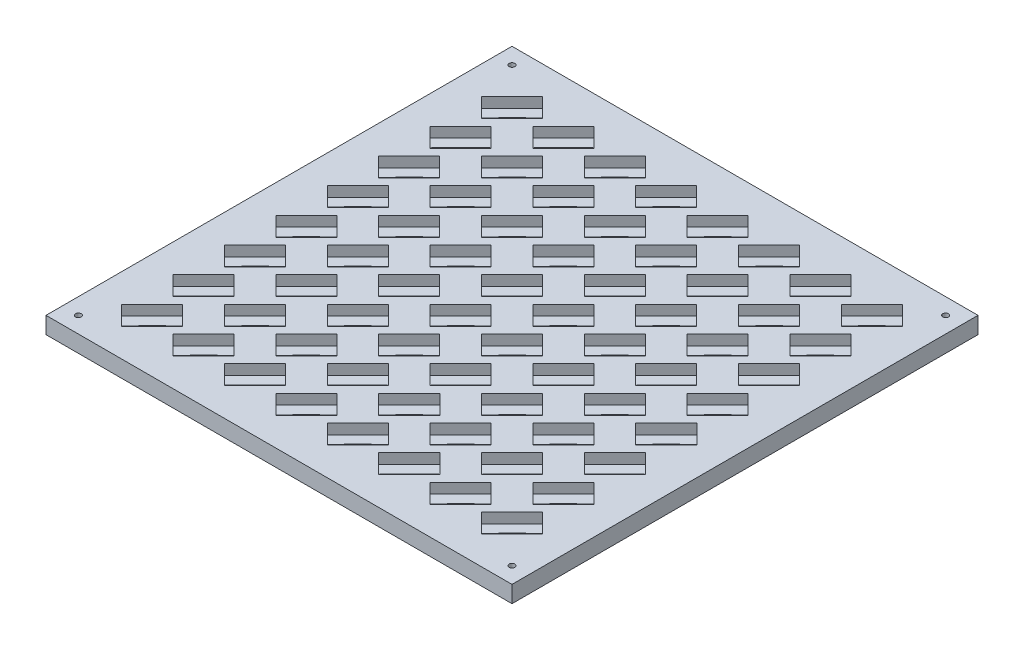
SolidWorks part; units mm, degrees
material "Acrylic (Medium-high impact)"
ref_plane "Front Plane" through (0, 0, 0) normal (0, 0, 1) x (1, 0, 0)
ref_plane "Top Plane" through (0, 0, 0) normal (0, 1, 0) x (1, 0, 0)
ref_plane "Right Plane" through (0, 0, 0) normal (1, 0, 0) x (0, 0, -1)
sketch "Sketch1" plane through (0, 0, 0) normal (0, 1, 0) x (1, 0, 0)
  line L1 (0, 0) -> (431.8, 0)
  line L2 (0, 0) -> (0, 431.8)
  line L3 (0, 431.8) -> (431.8, 431.8)
  line L4 (431.8, 0) -> (431.8, 431.8)
  dimension "D1" = 431.8
  dimension "D2" = 431.8
extrude "Boss-Extrude1" add sketch "Sketch1" along normal blind 6
sketch "Sketch2" plane through (0, 6, 0) normal (0, 1, 0) x (1, 0, 0)
  line L0 (73.025, 25.4) -> (73.025, 73.025) construction
  line L1 (25.4, 25.4) -> (73.025, 25.4) construction
  line L2 (25.4, 25.4) -> (25.4, 73.025) construction
  line L3 (25.4, 73.025) -> (73.025, 73.025) construction
  line L4 (73.025, 25.4) -> (73.025, 73.025) construction
  line L5 (73.025, 25.4) -> (120.65, 25.4) construction
  line L6 (120.65, 25.4) -> (120.65, 73.025) construction
  line L7 (73.025, 73.025) -> (120.65, 73.025) construction
  line L8 (120.65, 25.4) -> (120.65, 73.025) construction
  line L9 (120.65, 25.4) -> (168.275, 25.4) construction
  line L10 (168.275, 25.4) -> (168.275, 73.025) construction
  line L11 (120.65, 73.025) -> (168.275, 73.025) construction
  line L12 (168.275, 25.4) -> (168.275, 73.025) construction
  line L13 (168.275, 25.4) -> (215.9, 25.4) construction
  line L14 (215.9, 25.4) -> (215.9, 73.025) construction
  line L15 (168.275, 73.025) -> (215.9, 73.025) construction
  line L16 (215.9, 25.4) -> (215.9, 73.025) construction
  line L17 (215.9, 25.4) -> (263.525, 25.4) construction
  line L18 (263.525, 25.4) -> (263.525, 73.025) construction
  line L19 (215.9, 73.025) -> (263.525, 73.025) construction
  line L20 (263.525, 25.4) -> (263.525, 73.025) construction
  line L21 (263.525, 25.4) -> (311.15, 25.4) construction
  line L22 (311.15, 25.4) -> (311.15, 73.025) construction
  line L23 (263.525, 73.025) -> (311.15, 73.025) construction
  line L24 (311.15, 25.4) -> (311.15, 73.025) construction
  line L25 (311.15, 25.4) -> (358.775, 25.4) construction
  line L26 (358.775, 25.4) -> (358.775, 73.025) construction
  line L27 (311.15, 73.025) -> (358.775, 73.025) construction
  line L28 (358.775, 25.4) -> (358.775, 73.025) construction
  line L29 (358.775, 25.4) -> (406.4, 25.4) construction
  line L30 (406.4, 25.4) -> (406.4, 73.025) construction
  line L31 (358.775, 73.025) -> (406.4, 73.025) construction
  line L32 (73.025, 73.025) -> (73.025, 120.65) construction
  line L33 (73.025, 73.025) -> (120.65, 73.025) construction
  line L34 (120.65, 73.025) -> (120.65, 120.65) construction
  line L35 (73.025, 120.65) -> (120.65, 120.65) construction
  line L36 (120.65, 73.025) -> (120.65, 120.65) construction
  line L37 (120.65, 73.025) -> (168.275, 73.025) construction
  line L38 (168.275, 73.025) -> (168.275, 120.65) construction
  line L39 (120.65, 120.65) -> (168.275, 120.65) construction
  line L40 (168.275, 73.025) -> (168.275, 120.65) construction
  line L41 (168.275, 73.025) -> (215.9, 73.025) construction
  line L42 (215.9, 73.025) -> (215.9, 120.65) construction
  line L43 (168.275, 120.65) -> (215.9, 120.65) construction
  line L44 (215.9, 73.025) -> (215.9, 120.65) construction
  line L45 (215.9, 73.025) -> (263.525, 73.025) construction
  line L46 (263.525, 73.025) -> (263.525, 120.65) construction
  line L47 (215.9, 120.65) -> (263.525, 120.65) construction
  line L48 (263.525, 73.025) -> (263.525, 120.65) construction
  line L49 (263.525, 73.025) -> (311.15, 73.025) construction
  line L50 (311.15, 73.025) -> (311.15, 120.65) construction
  line L51 (263.525, 120.65) -> (311.15, 120.65) construction
  line L52 (311.15, 73.025) -> (311.15, 120.65) construction
  line L53 (311.15, 73.025) -> (358.775, 73.025) construction
  line L54 (358.775, 73.025) -> (358.775, 120.65) construction
  line L55 (311.15, 120.65) -> (358.775, 120.65) construction
  line L56 (358.775, 73.025) -> (358.775, 120.65) construction
  line L57 (358.775, 73.025) -> (406.4, 73.025) construction
  line L58 (406.4, 73.025) -> (406.4, 120.65) construction
  line L59 (358.775, 120.65) -> (406.4, 120.65) construction
  line L60 (73.025, 120.65) -> (73.025, 168.275) construction
  line L61 (73.025, 120.65) -> (120.65, 120.65) construction
  line L62 (120.65, 120.65) -> (120.65, 168.275) construction
  line L63 (73.025, 168.275) -> (120.65, 168.275) construction
  line L64 (120.65, 120.65) -> (120.65, 168.275) construction
  line L65 (120.65, 120.65) -> (168.275, 120.65) construction
  line L66 (168.275, 120.65) -> (168.275, 168.275) construction
  line L67 (120.65, 168.275) -> (168.275, 168.275) construction
  line L68 (168.275, 120.65) -> (168.275, 168.275) construction
  line L69 (168.275, 120.65) -> (215.9, 120.65) construction
  line L70 (215.9, 120.65) -> (215.9, 168.275) construction
  line L71 (168.275, 168.275) -> (215.9, 168.275) construction
  line L72 (215.9, 120.65) -> (215.9, 168.275) construction
  line L73 (215.9, 120.65) -> (263.525, 120.65) construction
  line L74 (263.525, 120.65) -> (263.525, 168.275) construction
  line L75 (215.9, 168.275) -> (263.525, 168.275) construction
  line L76 (263.525, 120.65) -> (263.525, 168.275) construction
  line L77 (263.525, 120.65) -> (311.15, 120.65) construction
  line L78 (311.15, 120.65) -> (311.15, 168.275) construction
  line L79 (263.525, 168.275) -> (311.15, 168.275) construction
  line L80 (311.15, 120.65) -> (311.15, 168.275) construction
  line L81 (311.15, 120.65) -> (358.775, 120.65) construction
  line L82 (358.775, 120.65) -> (358.775, 168.275) construction
  line L83 (311.15, 168.275) -> (358.775, 168.275) construction
  line L84 (358.775, 120.65) -> (358.775, 168.275) construction
  line L85 (358.775, 120.65) -> (406.4, 120.65) construction
  line L86 (406.4, 120.65) -> (406.4, 168.275) construction
  line L87 (358.775, 168.275) -> (406.4, 168.275) construction
  line L88 (73.025, 168.275) -> (73.025, 215.9) construction
  line L89 (73.025, 168.275) -> (120.65, 168.275) construction
  line L90 (120.65, 168.275) -> (120.65, 215.9) construction
  line L91 (73.025, 215.9) -> (120.65, 215.9) construction
  line L92 (120.65, 168.275) -> (120.65, 215.9) construction
  line L93 (120.65, 168.275) -> (168.275, 168.275) construction
  line L94 (168.275, 168.275) -> (168.275, 215.9) construction
  line L95 (120.65, 215.9) -> (168.275, 215.9) construction
  line L96 (168.275, 168.275) -> (168.275, 215.9) construction
  line L97 (168.275, 168.275) -> (215.9, 168.275) construction
  line L98 (215.9, 168.275) -> (215.9, 215.9) construction
  line L99 (168.275, 215.9) -> (215.9, 215.9) construction
  line L100 (215.9, 168.275) -> (215.9, 215.9) construction
  line L101 (215.9, 168.275) -> (263.525, 168.275) construction
  line L102 (263.525, 168.275) -> (263.525, 215.9) construction
  line L103 (215.9, 215.9) -> (263.525, 215.9) construction
  line L104 (263.525, 168.275) -> (263.525, 215.9) construction
  line L105 (263.525, 168.275) -> (311.15, 168.275) construction
  line L106 (311.15, 168.275) -> (311.15, 215.9) construction
  line L107 (263.525, 215.9) -> (311.15, 215.9) construction
  line L108 (311.15, 168.275) -> (311.15, 215.9) construction
  line L109 (311.15, 168.275) -> (358.775, 168.275) construction
  line L110 (358.775, 168.275) -> (358.775, 215.9) construction
  line L111 (311.15, 215.9) -> (358.775, 215.9) construction
  line L112 (358.775, 168.275) -> (358.775, 215.9) construction
  line L113 (358.775, 168.275) -> (406.4, 168.275) construction
  line L114 (406.4, 168.275) -> (406.4, 215.9) construction
  line L115 (358.775, 215.9) -> (406.4, 215.9) construction
  line L116 (73.025, 215.9) -> (73.025, 263.525) construction
  line L117 (73.025, 215.9) -> (120.65, 215.9) construction
  line L118 (120.65, 215.9) -> (120.65, 263.525) construction
  line L119 (73.025, 263.525) -> (120.65, 263.525) construction
  line L120 (120.65, 215.9) -> (120.65, 263.525) construction
  line L121 (120.65, 215.9) -> (168.275, 215.9) construction
  line L122 (168.275, 215.9) -> (168.275, 263.525) construction
  line L123 (120.65, 263.525) -> (168.275, 263.525) construction
  line L124 (168.275, 215.9) -> (168.275, 263.525) construction
  line L125 (168.275, 215.9) -> (215.9, 215.9) construction
  line L126 (215.9, 215.9) -> (215.9, 263.525) construction
  line L127 (168.275, 263.525) -> (215.9, 263.525) construction
  line L128 (215.9, 215.9) -> (215.9, 263.525) construction
  line L129 (215.9, 215.9) -> (263.525, 215.9) construction
  line L130 (263.525, 215.9) -> (263.525, 263.525) construction
  line L131 (215.9, 263.525) -> (263.525, 263.525) construction
  line L132 (263.525, 215.9) -> (263.525, 263.525) construction
  line L133 (263.525, 215.9) -> (311.15, 215.9) construction
  line L134 (311.15, 215.9) -> (311.15, 263.525) construction
  line L135 (263.525, 263.525) -> (311.15, 263.525) construction
  line L136 (311.15, 215.9) -> (311.15, 263.525) construction
  line L137 (311.15, 215.9) -> (358.775, 215.9) construction
  line L138 (358.775, 215.9) -> (358.775, 263.525) construction
  line L139 (311.15, 263.525) -> (358.775, 263.525) construction
  line L140 (358.775, 215.9) -> (358.775, 263.525) construction
  line L141 (358.775, 215.9) -> (406.4, 215.9) construction
  line L142 (406.4, 215.9) -> (406.4, 263.525) construction
  line L143 (358.775, 263.525) -> (406.4, 263.525) construction
  line L144 (73.025, 263.525) -> (73.025, 311.15) construction
  line L145 (73.025, 263.525) -> (120.65, 263.525) construction
  line L146 (120.65, 263.525) -> (120.65, 311.15) construction
  line L147 (73.025, 311.15) -> (120.65, 311.15) construction
  line L148 (120.65, 263.525) -> (120.65, 311.15) construction
  line L149 (120.65, 263.525) -> (168.275, 263.525) construction
  line L150 (168.275, 263.525) -> (168.275, 311.15) construction
  line L151 (120.65, 311.15) -> (168.275, 311.15) construction
  line L152 (168.275, 263.525) -> (168.275, 311.15) construction
  line L153 (168.275, 263.525) -> (215.9, 263.525) construction
  line L154 (215.9, 263.525) -> (215.9, 311.15) construction
  line L155 (168.275, 311.15) -> (215.9, 311.15) construction
  line L156 (215.9, 263.525) -> (215.9, 311.15) construction
  line L157 (215.9, 263.525) -> (263.525, 263.525) construction
  line L158 (263.525, 263.525) -> (263.525, 311.15) construction
  line L159 (215.9, 311.15) -> (263.525, 311.15) construction
  line L160 (263.525, 263.525) -> (263.525, 311.15) construction
  line L161 (263.525, 263.525) -> (311.15, 263.525) construction
  line L162 (311.15, 263.525) -> (311.15, 311.15) construction
  line L163 (263.525, 311.15) -> (311.15, 311.15) construction
  line L164 (311.15, 263.525) -> (311.15, 311.15) construction
  line L165 (311.15, 263.525) -> (358.775, 263.525) construction
  line L166 (358.775, 263.525) -> (358.775, 311.15) construction
  line L167 (311.15, 311.15) -> (358.775, 311.15) construction
  line L168 (358.775, 263.525) -> (358.775, 311.15) construction
  line L169 (358.775, 263.525) -> (406.4, 263.525) construction
  line L170 (406.4, 263.525) -> (406.4, 311.15) construction
  line L171 (358.775, 311.15) -> (406.4, 311.15) construction
  line L172 (73.025, 311.15) -> (73.025, 358.775) construction
  line L173 (73.025, 311.15) -> (120.65, 311.15) construction
  line L174 (120.65, 311.15) -> (120.65, 358.775) construction
  line L175 (73.025, 358.775) -> (120.65, 358.775) construction
  line L176 (120.65, 311.15) -> (120.65, 358.775) construction
  line L177 (120.65, 311.15) -> (168.275, 311.15) construction
  line L178 (168.275, 311.15) -> (168.275, 358.775) construction
  line L179 (120.65, 358.775) -> (168.275, 358.775) construction
  line L180 (168.275, 311.15) -> (168.275, 358.775) construction
  line L181 (168.275, 311.15) -> (215.9, 311.15) construction
  line L182 (215.9, 311.15) -> (215.9, 358.775) construction
  line L183 (168.275, 358.775) -> (215.9, 358.775) construction
  line L184 (215.9, 311.15) -> (215.9, 358.775) construction
  line L185 (215.9, 311.15) -> (263.525, 311.15) construction
  line L186 (263.525, 311.15) -> (263.525, 358.775) construction
  line L187 (215.9, 358.775) -> (263.525, 358.775) construction
  line L188 (263.525, 311.15) -> (263.525, 358.775) construction
  line L189 (263.525, 311.15) -> (311.15, 311.15) construction
  line L190 (311.15, 311.15) -> (311.15, 358.775) construction
  line L191 (263.525, 358.775) -> (311.15, 358.775) construction
  line L192 (311.15, 311.15) -> (311.15, 358.775) construction
  line L193 (311.15, 311.15) -> (358.775, 311.15) construction
  line L194 (358.775, 311.15) -> (358.775, 358.775) construction
  line L195 (311.15, 358.775) -> (358.775, 358.775) construction
  line L196 (358.775, 311.15) -> (358.775, 358.775) construction
  line L197 (358.775, 311.15) -> (406.4, 311.15) construction
  line L198 (406.4, 311.15) -> (406.4, 358.775) construction
  line L199 (358.775, 358.775) -> (406.4, 358.775) construction
  line L200 (73.025, 358.775) -> (73.025, 406.4) construction
  line L201 (73.025, 358.775) -> (120.65, 358.775) construction
  line L202 (120.65, 358.775) -> (120.65, 406.4) construction
  line L203 (73.025, 406.4) -> (120.65, 406.4) construction
  line L204 (120.65, 358.775) -> (120.65, 406.4) construction
  line L205 (120.65, 358.775) -> (168.275, 358.775) construction
  line L206 (168.275, 358.775) -> (168.275, 406.4) construction
  line L207 (120.65, 406.4) -> (168.275, 406.4) construction
  line L208 (168.275, 358.775) -> (168.275, 406.4) construction
  line L209 (168.275, 358.775) -> (215.9, 358.775) construction
  line L210 (215.9, 358.775) -> (215.9, 406.4) construction
  line L211 (168.275, 406.4) -> (215.9, 406.4) construction
  line L212 (215.9, 358.775) -> (215.9, 406.4) construction
  line L213 (215.9, 358.775) -> (263.525, 358.775) construction
  line L214 (263.525, 358.775) -> (263.525, 406.4) construction
  line L215 (215.9, 406.4) -> (263.525, 406.4) construction
  line L216 (263.525, 358.775) -> (263.525, 406.4) construction
  line L217 (263.525, 358.775) -> (311.15, 358.775) construction
  line L218 (311.15, 358.775) -> (311.15, 406.4) construction
  line L219 (263.525, 406.4) -> (311.15, 406.4) construction
  line L220 (311.15, 358.775) -> (311.15, 406.4) construction
  line L221 (311.15, 358.775) -> (358.775, 358.775) construction
  line L222 (358.775, 358.775) -> (358.775, 406.4) construction
  line L223 (311.15, 406.4) -> (358.775, 406.4) construction
  line L224 (358.775, 358.775) -> (358.775, 406.4) construction
  line L225 (358.775, 358.775) -> (406.4, 358.775) construction
  line L226 (406.4, 358.775) -> (406.4, 406.4) construction
  line L227 (358.775, 406.4) -> (406.4, 406.4) construction
  line L228 (25.4, 73.025) -> (25.4, 120.65) construction
  line L229 (25.4, 73.025) -> (73.025, 73.025) construction
  line L230 (73.025, 73.025) -> (73.025, 120.65) construction
  line L231 (25.4, 120.65) -> (73.025, 120.65) construction
  line L232 (25.4, 120.65) -> (25.4, 168.275) construction
  line L233 (25.4, 120.65) -> (73.025, 120.65) construction
  line L234 (73.025, 120.65) -> (73.025, 168.275) construction
  line L235 (25.4, 168.275) -> (73.025, 168.275) construction
  line L236 (25.4, 168.275) -> (25.4, 215.9) construction
  line L237 (25.4, 168.275) -> (73.025, 168.275) construction
  line L238 (73.025, 168.275) -> (73.025, 215.9) construction
  line L239 (25.4, 215.9) -> (73.025, 215.9) construction
  line L240 (25.4, 215.9) -> (25.4, 263.525) construction
  line L241 (25.4, 215.9) -> (73.025, 215.9) construction
  line L242 (73.025, 215.9) -> (73.025, 263.525) construction
  line L243 (25.4, 263.525) -> (73.025, 263.525) construction
  line L244 (25.4, 263.525) -> (25.4, 311.15) construction
  line L245 (25.4, 263.525) -> (73.025, 263.525) construction
  line L246 (73.025, 263.525) -> (73.025, 311.15) construction
  line L247 (25.4, 311.15) -> (73.025, 311.15) construction
  line L248 (25.4, 311.15) -> (25.4, 358.775) construction
  line L249 (25.4, 311.15) -> (73.025, 311.15) construction
  line L250 (73.025, 311.15) -> (73.025, 358.775) construction
  line L251 (25.4, 358.775) -> (73.025, 358.775) construction
  line L252 (25.4, 358.775) -> (25.4, 406.4) construction
  line L253 (25.4, 358.775) -> (73.025, 358.775) construction
  line L254 (73.025, 358.775) -> (73.025, 406.4) construction
  line L255 (25.4, 406.4) -> (73.025, 406.4) construction
  line L256 (0, 0) -> (431.8, 0) construction
  line L257 (0, 431.8) -> (0, 0) construction
  line L259 (431.8, 431.8) -> (0, 431.8) construction
  line L260 (431.8, 0) -> (431.8, 431.8) construction
  line L261 (73.025, 73.025) -> (25.4, 25.4) construction
  line L266 (41.7253, 43.9704) -> (34.6543, 36.8993)
  line L906 (56.99, 54.1616) -> (56.6983, 54.4532)
  line L922 (56.99, 54.1616) -> (44.2621, 41.4336)
  line L923 (44.2621, 41.4336) -> (43.9704, 41.7253)
  line L924 (54.1616, 56.99) -> (41.4336, 44.2621)
  line L925 (34.6543, 36.8993) -> (36.8993, 34.6543)
  line L926 (36.8993, 34.6543) -> (43.9704, 41.7253)
  line L927 (41.7253, 43.9704) -> (41.4336, 44.2621)
  line L928 (54.4532, 56.6983) -> (61.5243, 63.7694)
  line L929 (61.5243, 63.7694) -> (63.7694, 61.5243)
  line L930 (63.7694, 61.5243) -> (56.6983, 54.4532)
  line L931 (54.4532, 56.6983) -> (54.1616, 56.99)
  line L932 (25.4, 73.025) -> (73.025, 25.4) construction
  line L933 (56.99, 101.7916) -> (56.6983, 102.0832)
  line L934 (63.7694, 109.1543) -> (56.6983, 102.0832)
  line L935 (61.5243, 111.3994) -> (63.7694, 109.1543)
  line L936 (54.4532, 104.3283) -> (61.5243, 111.3994)
  line L937 (54.4532, 104.3283) -> (54.1616, 104.62)
  line L938 (54.1616, 104.62) -> (41.4336, 91.8921)
  line L939 (41.7253, 91.6004) -> (41.4336, 91.8921)
  line L940 (41.7253, 91.6004) -> (34.6543, 84.5293)
  line L941 (34.6543, 84.5293) -> (36.8993, 82.2843)
  line L942 (36.8993, 82.2843) -> (43.9704, 89.3553)
  line L943 (44.2621, 89.0636) -> (43.9704, 89.3553)
  line L944 (56.99, 101.7916) -> (44.2621, 89.0636)
  line L945 (56.99, 149.4216) -> (56.6983, 149.7132)
  line L946 (63.7694, 156.7843) -> (56.6983, 149.7132)
  line L947 (61.5243, 159.0294) -> (63.7694, 156.7843)
  line L948 (54.4532, 151.9583) -> (61.5243, 159.0294)
  line L949 (54.4532, 151.9583) -> (54.1616, 152.25)
  line L950 (54.1616, 152.25) -> (41.4336, 139.5221)
  line L951 (41.7253, 139.2304) -> (41.4336, 139.5221)
  line L952 (41.7253, 139.2304) -> (34.6543, 132.1593)
  line L953 (34.6543, 132.1593) -> (36.8993, 129.9143)
  line L954 (36.8993, 129.9143) -> (43.9704, 136.9853)
  line L955 (44.2621, 136.6936) -> (43.9704, 136.9853)
  line L956 (56.99, 149.4216) -> (44.2621, 136.6936)
  line L957 (56.99, 197.0516) -> (56.6983, 197.3432)
  line L958 (63.7694, 204.4143) -> (56.6983, 197.3432)
  line L959 (61.5243, 206.6594) -> (63.7694, 204.4143)
  line L960 (54.4532, 199.5883) -> (61.5243, 206.6594)
  line L961 (54.4532, 199.5883) -> (54.1616, 199.88)
  line L962 (54.1616, 199.88) -> (41.4336, 187.1521)
  line L963 (41.7253, 186.8604) -> (41.4336, 187.1521)
  line L964 (41.7253, 186.8604) -> (34.6543, 179.7893)
  line L965 (34.6543, 179.7893) -> (36.8993, 177.5443)
  line L966 (36.8993, 177.5443) -> (43.9704, 184.6153)
  line L967 (44.2621, 184.3236) -> (43.9704, 184.6153)
  line L968 (56.99, 197.0516) -> (44.2621, 184.3236)
  line L969 (56.99, 244.6816) -> (56.6983, 244.9732)
  line L970 (63.7694, 252.0443) -> (56.6983, 244.9732)
  line L971 (61.5243, 254.2894) -> (63.7694, 252.0443)
  line L972 (54.4532, 247.2183) -> (61.5243, 254.2894)
  line L973 (54.4532, 247.2183) -> (54.1616, 247.51)
  line L974 (54.1616, 247.51) -> (41.4336, 234.7821)
  line L975 (41.7253, 234.4904) -> (41.4336, 234.7821)
  line L976 (41.7253, 234.4904) -> (34.6543, 227.4193)
  line L977 (34.6543, 227.4193) -> (36.8993, 225.1743)
  line L978 (36.8993, 225.1743) -> (43.9704, 232.2453)
  line L979 (44.2621, 231.9536) -> (43.9704, 232.2453)
  line L980 (56.99, 244.6816) -> (44.2621, 231.9536)
  line L981 (56.99, 292.3116) -> (56.6983, 292.6032)
  line L982 (63.7694, 299.6743) -> (56.6983, 292.6032)
  line L983 (61.5243, 301.9194) -> (63.7694, 299.6743)
  line L984 (54.4532, 294.8483) -> (61.5243, 301.9194)
  line L985 (54.4532, 294.8483) -> (54.1616, 295.14)
  line L986 (54.1616, 295.14) -> (41.4336, 282.4121)
  line L987 (41.7253, 282.1204) -> (41.4336, 282.4121)
  line L988 (41.7253, 282.1204) -> (34.6543, 275.0493)
  line L989 (34.6543, 275.0493) -> (36.8993, 272.8043)
  line L990 (36.8993, 272.8043) -> (43.9704, 279.8753)
  line L991 (44.2621, 279.5836) -> (43.9704, 279.8753)
  line L992 (56.99, 292.3116) -> (44.2621, 279.5836)
  line L993 (56.99, 339.9416) -> (56.6983, 340.2332)
  line L994 (63.7694, 347.3043) -> (56.6983, 340.2332)
  line L995 (61.5243, 349.5494) -> (63.7694, 347.3043)
  line L996 (54.4532, 342.4783) -> (61.5243, 349.5494)
  line L997 (54.4532, 342.4783) -> (54.1616, 342.77)
  line L998 (54.1616, 342.77) -> (41.4336, 330.0421)
  line L999 (41.7253, 329.7504) -> (41.4336, 330.0421)
  line L1000 (41.7253, 329.7504) -> (34.6543, 322.6793)
  line L1001 (34.6543, 322.6793) -> (36.8993, 320.4343)
  line L1002 (36.8993, 320.4343) -> (43.9704, 327.5053)
  line L1003 (44.2621, 327.2136) -> (43.9704, 327.5053)
  line L1004 (56.99, 339.9416) -> (44.2621, 327.2136)
  line L1005 (56.99, 387.5716) -> (56.6983, 387.8632)
  line L1006 (63.7694, 394.9343) -> (56.6983, 387.8632)
  line L1007 (61.5243, 397.1794) -> (63.7694, 394.9343)
  line L1008 (54.4532, 390.1083) -> (61.5243, 397.1794)
  line L1009 (54.4532, 390.1083) -> (54.1616, 390.4)
  line L1010 (54.1616, 390.4) -> (41.4336, 377.6721)
  line L1011 (41.7253, 377.3804) -> (41.4336, 377.6721)
  line L1012 (41.7253, 377.3804) -> (34.6543, 370.3093)
  line L1013 (34.6543, 370.3093) -> (36.8993, 368.0643)
  line L1014 (36.8993, 368.0643) -> (43.9704, 375.1353)
  line L1015 (44.2621, 374.8436) -> (43.9704, 375.1353)
  line L1016 (56.99, 387.5716) -> (44.2621, 374.8436)
  line L1017 (104.62, 101.7916) -> (104.3283, 102.0832)
  line L1018 (111.3994, 109.1543) -> (104.3283, 102.0832)
  line L1019 (109.1543, 111.3994) -> (111.3994, 109.1543)
  line L1020 (102.0832, 104.3283) -> (109.1543, 111.3994)
  line L1021 (102.0832, 104.3283) -> (101.7916, 104.62)
  line L1022 (101.7916, 104.62) -> (89.0636, 91.8921)
  line L1023 (89.3553, 91.6004) -> (89.0636, 91.8921)
  line L1024 (89.3553, 91.6004) -> (82.2843, 84.5293)
  line L1025 (82.2843, 84.5293) -> (84.5293, 82.2843)
  line L1026 (84.5293, 82.2843) -> (91.6004, 89.3553)
  line L1027 (91.8921, 89.0636) -> (91.6004, 89.3553)
  line L1028 (104.62, 101.7916) -> (91.8921, 89.0636)
  line L1029 (104.62, 149.4216) -> (104.3283, 149.7132)
  line L1030 (111.3994, 156.7843) -> (104.3283, 149.7132)
  line L1031 (109.1543, 159.0294) -> (111.3994, 156.7843)
  line L1032 (102.0832, 151.9583) -> (109.1543, 159.0294)
  line L1033 (102.0832, 151.9583) -> (101.7916, 152.25)
  line L1034 (101.7916, 152.25) -> (89.0636, 139.5221)
  line L1035 (89.3553, 139.2304) -> (89.0636, 139.5221)
  line L1036 (89.3553, 139.2304) -> (82.2843, 132.1593)
  line L1037 (82.2843, 132.1593) -> (84.5293, 129.9143)
  line L1038 (84.5293, 129.9143) -> (91.6004, 136.9853)
  line L1039 (91.8921, 136.6936) -> (91.6004, 136.9853)
  line L1040 (104.62, 149.4216) -> (91.8921, 136.6936)
  line L1041 (104.62, 197.0516) -> (104.3283, 197.3432)
  line L1042 (111.3994, 204.4143) -> (104.3283, 197.3432)
  line L1043 (109.1543, 206.6594) -> (111.3994, 204.4143)
  line L1044 (102.0832, 199.5883) -> (109.1543, 206.6594)
  line L1045 (102.0832, 199.5883) -> (101.7916, 199.88)
  line L1046 (101.7916, 199.88) -> (89.0636, 187.1521)
  line L1047 (89.3553, 186.8604) -> (89.0636, 187.1521)
  line L1048 (89.3553, 186.8604) -> (82.2843, 179.7893)
  line L1049 (82.2843, 179.7893) -> (84.5293, 177.5443)
  line L1050 (84.5293, 177.5443) -> (91.6004, 184.6153)
  line L1051 (91.8921, 184.3236) -> (91.6004, 184.6153)
  line L1052 (104.62, 197.0516) -> (91.8921, 184.3236)
  line L1053 (104.62, 244.6816) -> (104.3283, 244.9732)
  line L1054 (111.3994, 252.0443) -> (104.3283, 244.9732)
  line L1055 (109.1543, 254.2894) -> (111.3994, 252.0443)
  line L1056 (102.0832, 247.2183) -> (109.1543, 254.2894)
  line L1057 (102.0832, 247.2183) -> (101.7916, 247.51)
  line L1058 (101.7916, 247.51) -> (89.0636, 234.7821)
  line L1059 (89.3553, 234.4904) -> (89.0636, 234.7821)
  line L1060 (89.3553, 234.4904) -> (82.2843, 227.4193)
  line L1061 (82.2843, 227.4193) -> (84.5293, 225.1743)
  line L1062 (84.5293, 225.1743) -> (91.6004, 232.2453)
  line L1063 (91.8921, 231.9536) -> (91.6004, 232.2453)
  line L1064 (104.62, 244.6816) -> (91.8921, 231.9536)
  line L1065 (104.62, 292.3116) -> (104.3283, 292.6032)
  line L1066 (111.3994, 299.6743) -> (104.3283, 292.6032)
  line L1067 (109.1543, 301.9194) -> (111.3994, 299.6743)
  line L1068 (102.0832, 294.8483) -> (109.1543, 301.9194)
  line L1069 (102.0832, 294.8483) -> (101.7916, 295.14)
  line L1070 (101.7916, 295.14) -> (89.0636, 282.4121)
  line L1071 (89.3553, 282.1204) -> (89.0636, 282.4121)
  line L1072 (89.3553, 282.1204) -> (82.2843, 275.0493)
  line L1073 (82.2843, 275.0493) -> (84.5293, 272.8043)
  line L1074 (84.5293, 272.8043) -> (91.6004, 279.8753)
  line L1075 (91.8921, 279.5836) -> (91.6004, 279.8753)
  line L1076 (104.62, 292.3116) -> (91.8921, 279.5836)
  line L1077 (104.62, 339.9416) -> (104.3283, 340.2332)
  line L1078 (111.3994, 347.3043) -> (104.3283, 340.2332)
  line L1079 (109.1543, 349.5494) -> (111.3994, 347.3043)
  line L1080 (102.0832, 342.4783) -> (109.1543, 349.5494)
  line L1081 (102.0832, 342.4783) -> (101.7916, 342.77)
  line L1082 (101.7916, 342.77) -> (89.0636, 330.0421)
  line L1083 (89.3553, 329.7504) -> (89.0636, 330.0421)
  line L1084 (89.3553, 329.7504) -> (82.2843, 322.6793)
  line L1085 (82.2843, 322.6793) -> (84.5293, 320.4343)
  line L1086 (84.5293, 320.4343) -> (91.6004, 327.5053)
  line L1087 (91.8921, 327.2136) -> (91.6004, 327.5053)
  line L1088 (104.62, 339.9416) -> (91.8921, 327.2136)
  line L1089 (104.62, 387.5716) -> (104.3283, 387.8632)
  line L1090 (111.3994, 394.9343) -> (104.3283, 387.8632)
  line L1091 (109.1543, 397.1794) -> (111.3994, 394.9343)
  line L1092 (102.0832, 390.1083) -> (109.1543, 397.1794)
  line L1093 (102.0832, 390.1083) -> (101.7916, 390.4)
  line L1094 (101.7916, 390.4) -> (89.0636, 377.6721)
  line L1095 (89.3553, 377.3804) -> (89.0636, 377.6721)
  line L1096 (89.3553, 377.3804) -> (82.2843, 370.3093)
  line L1097 (82.2843, 370.3093) -> (84.5293, 368.0643)
  line L1098 (84.5293, 368.0643) -> (91.6004, 375.1353)
  line L1099 (91.8921, 374.8436) -> (91.6004, 375.1353)
  line L1100 (104.62, 387.5716) -> (91.8921, 374.8436)
  line L1101 (152.25, 101.7916) -> (151.9583, 102.0832)
  line L1102 (159.0294, 109.1543) -> (151.9583, 102.0832)
  line L1103 (156.7843, 111.3994) -> (159.0294, 109.1543)
  line L1104 (149.7132, 104.3283) -> (156.7843, 111.3994)
  line L1105 (149.7132, 104.3283) -> (149.4216, 104.62)
  line L1106 (149.4216, 104.62) -> (136.6936, 91.8921)
  line L1107 (136.9853, 91.6004) -> (136.6936, 91.8921)
  line L1108 (136.9853, 91.6004) -> (129.9143, 84.5293)
  line L1109 (129.9143, 84.5293) -> (132.1593, 82.2843)
  line L1110 (132.1593, 82.2843) -> (139.2304, 89.3553)
  line L1111 (139.5221, 89.0636) -> (139.2304, 89.3553)
  line L1112 (152.25, 101.7916) -> (139.5221, 89.0636)
  line L1113 (152.25, 149.4216) -> (151.9583, 149.7132)
  line L1114 (159.0294, 156.7843) -> (151.9583, 149.7132)
  line L1115 (156.7843, 159.0294) -> (159.0294, 156.7843)
  line L1116 (149.7132, 151.9583) -> (156.7843, 159.0294)
  line L1117 (149.7132, 151.9583) -> (149.4216, 152.25)
  line L1118 (149.4216, 152.25) -> (136.6936, 139.5221)
  line L1119 (136.9853, 139.2304) -> (136.6936, 139.5221)
  line L1120 (136.9853, 139.2304) -> (129.9143, 132.1593)
  line L1121 (129.9143, 132.1593) -> (132.1593, 129.9143)
  line L1122 (132.1593, 129.9143) -> (139.2304, 136.9853)
  line L1123 (139.5221, 136.6936) -> (139.2304, 136.9853)
  line L1124 (152.25, 149.4216) -> (139.5221, 136.6936)
  line L1125 (152.25, 197.0516) -> (151.9583, 197.3432)
  line L1126 (159.0294, 204.4143) -> (151.9583, 197.3432)
  line L1127 (156.7843, 206.6594) -> (159.0294, 204.4143)
  line L1128 (149.7132, 199.5883) -> (156.7843, 206.6594)
  line L1129 (149.7132, 199.5883) -> (149.4216, 199.88)
  line L1130 (149.4216, 199.88) -> (136.6936, 187.1521)
  line L1131 (136.9853, 186.8604) -> (136.6936, 187.1521)
  line L1132 (136.9853, 186.8604) -> (129.9143, 179.7893)
  line L1133 (129.9143, 179.7893) -> (132.1593, 177.5443)
  line L1134 (132.1593, 177.5443) -> (139.2304, 184.6153)
  line L1135 (139.5221, 184.3236) -> (139.2304, 184.6153)
  line L1136 (152.25, 197.0516) -> (139.5221, 184.3236)
  line L1137 (152.25, 244.6816) -> (151.9583, 244.9732)
  line L1138 (159.0294, 252.0443) -> (151.9583, 244.9732)
  line L1139 (156.7843, 254.2894) -> (159.0294, 252.0443)
  line L1140 (149.7132, 247.2183) -> (156.7843, 254.2894)
  line L1141 (149.7132, 247.2183) -> (149.4216, 247.51)
  line L1142 (149.4216, 247.51) -> (136.6936, 234.7821)
  line L1143 (136.9853, 234.4904) -> (136.6936, 234.7821)
  line L1144 (136.9853, 234.4904) -> (129.9143, 227.4193)
  line L1145 (129.9143, 227.4193) -> (132.1593, 225.1743)
  line L1146 (132.1593, 225.1743) -> (139.2304, 232.2453)
  line L1147 (139.5221, 231.9536) -> (139.2304, 232.2453)
  line L1148 (152.25, 244.6816) -> (139.5221, 231.9536)
  line L1149 (152.25, 292.3116) -> (151.9583, 292.6032)
  line L1150 (159.0294, 299.6743) -> (151.9583, 292.6032)
  line L1151 (156.7843, 301.9194) -> (159.0294, 299.6743)
  line L1152 (149.7132, 294.8483) -> (156.7843, 301.9194)
  line L1153 (149.7132, 294.8483) -> (149.4216, 295.14)
  line L1154 (149.4216, 295.14) -> (136.6936, 282.4121)
  line L1155 (136.9853, 282.1204) -> (136.6936, 282.4121)
  line L1156 (136.9853, 282.1204) -> (129.9143, 275.0493)
  line L1157 (129.9143, 275.0493) -> (132.1593, 272.8043)
  line L1158 (132.1593, 272.8043) -> (139.2304, 279.8753)
  line L1159 (139.5221, 279.5836) -> (139.2304, 279.8753)
  line L1160 (152.25, 292.3116) -> (139.5221, 279.5836)
  line L1161 (152.25, 339.9416) -> (151.9583, 340.2332)
  line L1162 (159.0294, 347.3043) -> (151.9583, 340.2332)
  line L1163 (156.7843, 349.5494) -> (159.0294, 347.3043)
  line L1164 (149.7132, 342.4783) -> (156.7843, 349.5494)
  line L1165 (149.7132, 342.4783) -> (149.4216, 342.77)
  line L1166 (149.4216, 342.77) -> (136.6936, 330.0421)
  line L1167 (136.9853, 329.7504) -> (136.6936, 330.0421)
  line L1168 (136.9853, 329.7504) -> (129.9143, 322.6793)
  line L1169 (129.9143, 322.6793) -> (132.1593, 320.4343)
  line L1170 (132.1593, 320.4343) -> (139.2304, 327.5053)
  line L1171 (139.5221, 327.2136) -> (139.2304, 327.5053)
  line L1172 (152.25, 339.9416) -> (139.5221, 327.2136)
  line L1173 (152.25, 387.5716) -> (151.9583, 387.8632)
  line L1174 (159.0294, 394.9343) -> (151.9583, 387.8632)
  line L1175 (156.7843, 397.1794) -> (159.0294, 394.9343)
  line L1176 (149.7132, 390.1083) -> (156.7843, 397.1794)
  line L1177 (149.7132, 390.1083) -> (149.4216, 390.4)
  line L1178 (149.4216, 390.4) -> (136.6936, 377.6721)
  line L1179 (136.9853, 377.3804) -> (136.6936, 377.6721)
  line L1180 (136.9853, 377.3804) -> (129.9143, 370.3093)
  line L1181 (129.9143, 370.3093) -> (132.1593, 368.0643)
  line L1182 (132.1593, 368.0643) -> (139.2304, 375.1353)
  line L1183 (139.5221, 374.8436) -> (139.2304, 375.1353)
  line L1184 (152.25, 387.5716) -> (139.5221, 374.8436)
  line L1185 (199.88, 101.7916) -> (199.5883, 102.0832)
  line L1186 (206.6594, 109.1543) -> (199.5883, 102.0832)
  line L1187 (204.4143, 111.3994) -> (206.6594, 109.1543)
  line L1188 (197.3432, 104.3283) -> (204.4143, 111.3994)
  line L1189 (197.3432, 104.3283) -> (197.0516, 104.62)
  line L1190 (197.0516, 104.62) -> (184.3236, 91.8921)
  line L1191 (184.6153, 91.6004) -> (184.3236, 91.8921)
  line L1192 (184.6153, 91.6004) -> (177.5443, 84.5293)
  line L1193 (177.5443, 84.5293) -> (179.7893, 82.2843)
  line L1194 (179.7893, 82.2843) -> (186.8604, 89.3553)
  line L1195 (187.1521, 89.0636) -> (186.8604, 89.3553)
  line L1196 (199.88, 101.7916) -> (187.1521, 89.0636)
  line L1197 (199.88, 149.4216) -> (199.5883, 149.7132)
  line L1198 (206.6594, 156.7843) -> (199.5883, 149.7132)
  line L1199 (204.4143, 159.0294) -> (206.6594, 156.7843)
  line L1200 (197.3432, 151.9583) -> (204.4143, 159.0294)
  line L1201 (197.3432, 151.9583) -> (197.0516, 152.25)
  line L1202 (197.0516, 152.25) -> (184.3236, 139.5221)
  line L1203 (184.6153, 139.2304) -> (184.3236, 139.5221)
  line L1204 (184.6153, 139.2304) -> (177.5443, 132.1593)
  line L1205 (177.5443, 132.1593) -> (179.7893, 129.9143)
  line L1206 (179.7893, 129.9143) -> (186.8604, 136.9853)
  line L1207 (187.1521, 136.6936) -> (186.8604, 136.9853)
  line L1208 (199.88, 149.4216) -> (187.1521, 136.6936)
  line L1209 (199.88, 197.0516) -> (199.5883, 197.3432)
  line L1210 (206.6594, 204.4143) -> (199.5883, 197.3432)
  line L1211 (204.4143, 206.6594) -> (206.6594, 204.4143)
  line L1212 (197.3432, 199.5883) -> (204.4143, 206.6594)
  line L1213 (197.3432, 199.5883) -> (197.0516, 199.88)
  line L1214 (197.0516, 199.88) -> (184.3236, 187.1521)
  line L1215 (184.6153, 186.8604) -> (184.3236, 187.1521)
  line L1216 (184.6153, 186.8604) -> (177.5443, 179.7893)
  line L1217 (177.5443, 179.7893) -> (179.7893, 177.5443)
  line L1218 (179.7893, 177.5443) -> (186.8604, 184.6153)
  line L1219 (187.1521, 184.3236) -> (186.8604, 184.6153)
  line L1220 (199.88, 197.0516) -> (187.1521, 184.3236)
  line L1221 (199.88, 244.6816) -> (199.5883, 244.9732)
  line L1222 (206.6594, 252.0443) -> (199.5883, 244.9732)
  line L1223 (204.4143, 254.2894) -> (206.6594, 252.0443)
  line L1224 (197.3432, 247.2183) -> (204.4143, 254.2894)
  line L1225 (197.3432, 247.2183) -> (197.0516, 247.51)
  line L1226 (197.0516, 247.51) -> (184.3236, 234.7821)
  line L1227 (184.6153, 234.4904) -> (184.3236, 234.7821)
  line L1228 (184.6153, 234.4904) -> (177.5443, 227.4193)
  line L1229 (177.5443, 227.4193) -> (179.7893, 225.1743)
  line L1230 (179.7893, 225.1743) -> (186.8604, 232.2453)
  line L1231 (187.1521, 231.9536) -> (186.8604, 232.2453)
  line L1232 (199.88, 244.6816) -> (187.1521, 231.9536)
  line L1233 (199.88, 292.3116) -> (199.5883, 292.6032)
  line L1234 (206.6594, 299.6743) -> (199.5883, 292.6032)
  line L1235 (204.4143, 301.9194) -> (206.6594, 299.6743)
  line L1236 (197.3432, 294.8483) -> (204.4143, 301.9194)
  line L1237 (197.3432, 294.8483) -> (197.0516, 295.14)
  line L1238 (197.0516, 295.14) -> (184.3236, 282.4121)
  line L1239 (184.6153, 282.1204) -> (184.3236, 282.4121)
  line L1240 (184.6153, 282.1204) -> (177.5443, 275.0493)
  line L1241 (177.5443, 275.0493) -> (179.7893, 272.8043)
  line L1242 (179.7893, 272.8043) -> (186.8604, 279.8753)
  line L1243 (187.1521, 279.5836) -> (186.8604, 279.8753)
  line L1244 (199.88, 292.3116) -> (187.1521, 279.5836)
  line L1245 (199.88, 339.9416) -> (199.5883, 340.2332)
  line L1246 (206.6594, 347.3043) -> (199.5883, 340.2332)
  line L1247 (204.4143, 349.5494) -> (206.6594, 347.3043)
  line L1248 (197.3432, 342.4783) -> (204.4143, 349.5494)
  line L1249 (197.3432, 342.4783) -> (197.0516, 342.77)
  line L1250 (197.0516, 342.77) -> (184.3236, 330.0421)
  line L1251 (184.6153, 329.7504) -> (184.3236, 330.0421)
  line L1252 (184.6153, 329.7504) -> (177.5443, 322.6793)
  line L1253 (177.5443, 322.6793) -> (179.7893, 320.4343)
  line L1254 (179.7893, 320.4343) -> (186.8604, 327.5053)
  line L1255 (187.1521, 327.2136) -> (186.8604, 327.5053)
  line L1256 (199.88, 339.9416) -> (187.1521, 327.2136)
  line L1257 (199.88, 387.5716) -> (199.5883, 387.8632)
  line L1258 (206.6594, 394.9343) -> (199.5883, 387.8632)
  line L1259 (204.4143, 397.1794) -> (206.6594, 394.9343)
  line L1260 (197.3432, 390.1083) -> (204.4143, 397.1794)
  line L1261 (197.3432, 390.1083) -> (197.0516, 390.4)
  line L1262 (197.0516, 390.4) -> (184.3236, 377.6721)
  line L1263 (184.6153, 377.3804) -> (184.3236, 377.6721)
  line L1264 (184.6153, 377.3804) -> (177.5443, 370.3093)
  line L1265 (177.5443, 370.3093) -> (179.7893, 368.0643)
  line L1266 (179.7893, 368.0643) -> (186.8604, 375.1353)
  line L1267 (187.1521, 374.8436) -> (186.8604, 375.1353)
  line L1268 (199.88, 387.5716) -> (187.1521, 374.8436)
  line L1269 (247.51, 101.7916) -> (247.2183, 102.0832)
  line L1270 (254.2894, 109.1543) -> (247.2183, 102.0832)
  line L1271 (252.0443, 111.3994) -> (254.2894, 109.1543)
  line L1272 (244.9732, 104.3283) -> (252.0443, 111.3994)
  line L1273 (244.9732, 104.3283) -> (244.6816, 104.62)
  line L1274 (244.6816, 104.62) -> (231.9536, 91.8921)
  line L1275 (232.2453, 91.6004) -> (231.9536, 91.8921)
  line L1276 (232.2453, 91.6004) -> (225.1743, 84.5293)
  line L1277 (225.1743, 84.5293) -> (227.4193, 82.2843)
  line L1278 (227.4193, 82.2843) -> (234.4904, 89.3553)
  line L1279 (234.7821, 89.0636) -> (234.4904, 89.3553)
  line L1280 (247.51, 101.7916) -> (234.7821, 89.0636)
  line L1281 (247.51, 149.4216) -> (247.2183, 149.7132)
  line L1282 (254.2894, 156.7843) -> (247.2183, 149.7132)
  line L1283 (252.0443, 159.0294) -> (254.2894, 156.7843)
  line L1284 (244.9732, 151.9583) -> (252.0443, 159.0294)
  line L1285 (244.9732, 151.9583) -> (244.6816, 152.25)
  line L1286 (244.6816, 152.25) -> (231.9536, 139.5221)
  line L1287 (232.2453, 139.2304) -> (231.9536, 139.5221)
  line L1288 (232.2453, 139.2304) -> (225.1743, 132.1593)
  line L1289 (225.1743, 132.1593) -> (227.4193, 129.9143)
  line L1290 (227.4193, 129.9143) -> (234.4904, 136.9853)
  line L1291 (234.7821, 136.6936) -> (234.4904, 136.9853)
  line L1292 (247.51, 149.4216) -> (234.7821, 136.6936)
  line L1293 (247.51, 197.0516) -> (247.2183, 197.3432)
  line L1294 (254.2894, 204.4143) -> (247.2183, 197.3432)
  line L1295 (252.0443, 206.6594) -> (254.2894, 204.4143)
  line L1296 (244.9732, 199.5883) -> (252.0443, 206.6594)
  line L1297 (244.9732, 199.5883) -> (244.6816, 199.88)
  line L1298 (244.6816, 199.88) -> (231.9536, 187.1521)
  line L1299 (232.2453, 186.8604) -> (231.9536, 187.1521)
  line L1300 (232.2453, 186.8604) -> (225.1743, 179.7893)
  line L1301 (225.1743, 179.7893) -> (227.4193, 177.5443)
  line L1302 (227.4193, 177.5443) -> (234.4904, 184.6153)
  line L1303 (234.7821, 184.3236) -> (234.4904, 184.6153)
  line L1304 (247.51, 197.0516) -> (234.7821, 184.3236)
  line L1305 (247.51, 244.6816) -> (247.2183, 244.9732)
  line L1306 (254.2894, 252.0443) -> (247.2183, 244.9732)
  line L1307 (252.0443, 254.2894) -> (254.2894, 252.0443)
  line L1308 (244.9732, 247.2183) -> (252.0443, 254.2894)
  line L1309 (244.9732, 247.2183) -> (244.6816, 247.51)
  line L1310 (244.6816, 247.51) -> (231.9536, 234.7821)
  line L1311 (232.2453, 234.4904) -> (231.9536, 234.7821)
  line L1312 (232.2453, 234.4904) -> (225.1743, 227.4193)
  line L1313 (225.1743, 227.4193) -> (227.4193, 225.1743)
  line L1314 (227.4193, 225.1743) -> (234.4904, 232.2453)
  line L1315 (234.7821, 231.9536) -> (234.4904, 232.2453)
  line L1316 (247.51, 244.6816) -> (234.7821, 231.9536)
  line L1317 (247.51, 292.3116) -> (247.2183, 292.6032)
  line L1318 (254.2894, 299.6743) -> (247.2183, 292.6032)
  line L1319 (252.0443, 301.9194) -> (254.2894, 299.6743)
  line L1320 (244.9732, 294.8483) -> (252.0443, 301.9194)
  line L1321 (244.9732, 294.8483) -> (244.6816, 295.14)
  line L1322 (244.6816, 295.14) -> (231.9536, 282.4121)
  line L1323 (232.2453, 282.1204) -> (231.9536, 282.4121)
  line L1324 (232.2453, 282.1204) -> (225.1743, 275.0493)
  line L1325 (225.1743, 275.0493) -> (227.4193, 272.8043)
  line L1326 (227.4193, 272.8043) -> (234.4904, 279.8753)
  line L1327 (234.7821, 279.5836) -> (234.4904, 279.8753)
  line L1328 (247.51, 292.3116) -> (234.7821, 279.5836)
  line L1329 (247.51, 339.9416) -> (247.2183, 340.2332)
  line L1330 (254.2894, 347.3043) -> (247.2183, 340.2332)
  line L1331 (252.0443, 349.5494) -> (254.2894, 347.3043)
  line L1332 (244.9732, 342.4783) -> (252.0443, 349.5494)
  line L1333 (244.9732, 342.4783) -> (244.6816, 342.77)
  line L1334 (244.6816, 342.77) -> (231.9536, 330.0421)
  line L1335 (232.2453, 329.7504) -> (231.9536, 330.0421)
  line L1336 (232.2453, 329.7504) -> (225.1743, 322.6793)
  line L1337 (225.1743, 322.6793) -> (227.4193, 320.4343)
  line L1338 (227.4193, 320.4343) -> (234.4904, 327.5053)
  line L1339 (234.7821, 327.2136) -> (234.4904, 327.5053)
  line L1340 (247.51, 339.9416) -> (234.7821, 327.2136)
  line L1341 (247.51, 387.5716) -> (247.2183, 387.8632)
  line L1342 (254.2894, 394.9343) -> (247.2183, 387.8632)
  line L1343 (252.0443, 397.1794) -> (254.2894, 394.9343)
  line L1344 (244.9732, 390.1083) -> (252.0443, 397.1794)
  line L1345 (244.9732, 390.1083) -> (244.6816, 390.4)
  line L1346 (244.6816, 390.4) -> (231.9536, 377.6721)
  line L1347 (232.2453, 377.3804) -> (231.9536, 377.6721)
  line L1348 (232.2453, 377.3804) -> (225.1743, 370.3093)
  line L1349 (225.1743, 370.3093) -> (227.4193, 368.0643)
  line L1350 (227.4193, 368.0643) -> (234.4904, 375.1353)
  line L1351 (234.7821, 374.8436) -> (234.4904, 375.1353)
  line L1352 (247.51, 387.5716) -> (234.7821, 374.8436)
  line L1353 (295.14, 101.7916) -> (294.8483, 102.0832)
  line L1354 (301.9194, 109.1543) -> (294.8483, 102.0832)
  line L1355 (299.6743, 111.3994) -> (301.9194, 109.1543)
  line L1356 (292.6032, 104.3283) -> (299.6743, 111.3994)
  line L1357 (292.6032, 104.3283) -> (292.3116, 104.62)
  line L1358 (292.3116, 104.62) -> (279.5836, 91.8921)
  line L1359 (279.8753, 91.6004) -> (279.5836, 91.8921)
  line L1360 (279.8753, 91.6004) -> (272.8043, 84.5293)
  line L1361 (272.8043, 84.5293) -> (275.0493, 82.2843)
  line L1362 (275.0493, 82.2843) -> (282.1204, 89.3553)
  line L1363 (282.4121, 89.0636) -> (282.1204, 89.3553)
  line L1364 (295.14, 101.7916) -> (282.4121, 89.0636)
  line L1365 (295.14, 149.4216) -> (294.8483, 149.7132)
  line L1366 (301.9194, 156.7843) -> (294.8483, 149.7132)
  line L1367 (299.6743, 159.0294) -> (301.9194, 156.7843)
  line L1368 (292.6032, 151.9583) -> (299.6743, 159.0294)
  line L1369 (292.6032, 151.9583) -> (292.3116, 152.25)
  line L1370 (292.3116, 152.25) -> (279.5836, 139.5221)
  line L1371 (279.8753, 139.2304) -> (279.5836, 139.5221)
  line L1372 (279.8753, 139.2304) -> (272.8043, 132.1593)
  line L1373 (272.8043, 132.1593) -> (275.0493, 129.9143)
  line L1374 (275.0493, 129.9143) -> (282.1204, 136.9853)
  line L1375 (282.4121, 136.6936) -> (282.1204, 136.9853)
  line L1376 (295.14, 149.4216) -> (282.4121, 136.6936)
  line L1377 (295.14, 197.0516) -> (294.8483, 197.3432)
  line L1378 (301.9194, 204.4143) -> (294.8483, 197.3432)
  line L1379 (299.6743, 206.6594) -> (301.9194, 204.4143)
  line L1380 (292.6032, 199.5883) -> (299.6743, 206.6594)
  line L1381 (292.6032, 199.5883) -> (292.3116, 199.88)
  line L1382 (292.3116, 199.88) -> (279.5836, 187.1521)
  line L1383 (279.8753, 186.8604) -> (279.5836, 187.1521)
  line L1384 (279.8753, 186.8604) -> (272.8043, 179.7893)
  line L1385 (272.8043, 179.7893) -> (275.0493, 177.5443)
  line L1386 (275.0493, 177.5443) -> (282.1204, 184.6153)
  line L1387 (282.4121, 184.3236) -> (282.1204, 184.6153)
  line L1388 (295.14, 197.0516) -> (282.4121, 184.3236)
  line L1389 (295.14, 244.6816) -> (294.8483, 244.9732)
  line L1390 (301.9194, 252.0443) -> (294.8483, 244.9732)
  line L1391 (299.6743, 254.2894) -> (301.9194, 252.0443)
  line L1392 (292.6032, 247.2183) -> (299.6743, 254.2894)
  line L1393 (292.6032, 247.2183) -> (292.3116, 247.51)
  line L1394 (292.3116, 247.51) -> (279.5836, 234.7821)
  line L1395 (279.8753, 234.4904) -> (279.5836, 234.7821)
  line L1396 (279.8753, 234.4904) -> (272.8043, 227.4193)
  line L1397 (272.8043, 227.4193) -> (275.0493, 225.1743)
  line L1398 (275.0493, 225.1743) -> (282.1204, 232.2453)
  line L1399 (282.4121, 231.9536) -> (282.1204, 232.2453)
  line L1400 (295.14, 244.6816) -> (282.4121, 231.9536)
  line L1401 (295.14, 292.3116) -> (294.8483, 292.6032)
  line L1402 (301.9194, 299.6743) -> (294.8483, 292.6032)
  line L1403 (299.6743, 301.9194) -> (301.9194, 299.6743)
  line L1404 (292.6032, 294.8483) -> (299.6743, 301.9194)
  line L1405 (292.6032, 294.8483) -> (292.3116, 295.14)
  line L1406 (292.3116, 295.14) -> (279.5836, 282.4121)
  line L1407 (279.8753, 282.1204) -> (279.5836, 282.4121)
  line L1408 (279.8753, 282.1204) -> (272.8043, 275.0493)
  line L1409 (272.8043, 275.0493) -> (275.0493, 272.8043)
  line L1410 (275.0493, 272.8043) -> (282.1204, 279.8753)
  line L1411 (282.4121, 279.5836) -> (282.1204, 279.8753)
  line L1412 (295.14, 292.3116) -> (282.4121, 279.5836)
  line L1413 (295.14, 339.9416) -> (294.8483, 340.2332)
  line L1414 (301.9194, 347.3043) -> (294.8483, 340.2332)
  line L1415 (299.6743, 349.5494) -> (301.9194, 347.3043)
  line L1416 (292.6032, 342.4783) -> (299.6743, 349.5494)
  line L1417 (292.6032, 342.4783) -> (292.3116, 342.77)
  line L1418 (292.3116, 342.77) -> (279.5836, 330.0421)
  line L1419 (279.8753, 329.7504) -> (279.5836, 330.0421)
  line L1420 (279.8753, 329.7504) -> (272.8043, 322.6793)
  line L1421 (272.8043, 322.6793) -> (275.0493, 320.4343)
  line L1422 (275.0493, 320.4343) -> (282.1204, 327.5053)
  line L1423 (282.4121, 327.2136) -> (282.1204, 327.5053)
  line L1424 (295.14, 339.9416) -> (282.4121, 327.2136)
  line L1425 (295.14, 387.5716) -> (294.8483, 387.8632)
  line L1426 (301.9194, 394.9343) -> (294.8483, 387.8632)
  line L1427 (299.6743, 397.1794) -> (301.9194, 394.9343)
  line L1428 (292.6032, 390.1083) -> (299.6743, 397.1794)
  line L1429 (292.6032, 390.1083) -> (292.3116, 390.4)
  line L1430 (292.3116, 390.4) -> (279.5836, 377.6721)
  line L1431 (279.8753, 377.3804) -> (279.5836, 377.6721)
  line L1432 (279.8753, 377.3804) -> (272.8043, 370.3093)
  line L1433 (272.8043, 370.3093) -> (275.0493, 368.0643)
  line L1434 (275.0493, 368.0643) -> (282.1204, 375.1353)
  line L1435 (282.4121, 374.8436) -> (282.1204, 375.1353)
  line L1436 (295.14, 387.5716) -> (282.4121, 374.8436)
  line L1437 (342.77, 101.7916) -> (342.4783, 102.0832)
  line L1438 (349.5494, 109.1543) -> (342.4783, 102.0832)
  line L1439 (347.3043, 111.3994) -> (349.5494, 109.1543)
  line L1440 (340.2332, 104.3283) -> (347.3043, 111.3994)
  line L1441 (340.2332, 104.3283) -> (339.9416, 104.62)
  line L1442 (339.9416, 104.62) -> (327.2136, 91.8921)
  line L1443 (327.5053, 91.6004) -> (327.2136, 91.8921)
  line L1444 (327.5053, 91.6004) -> (320.4343, 84.5293)
  line L1445 (320.4343, 84.5293) -> (322.6793, 82.2843)
  line L1446 (322.6793, 82.2843) -> (329.7504, 89.3553)
  line L1447 (330.0421, 89.0636) -> (329.7504, 89.3553)
  line L1448 (342.77, 101.7916) -> (330.0421, 89.0636)
  line L1449 (342.77, 149.4216) -> (342.4783, 149.7132)
  line L1450 (349.5494, 156.7843) -> (342.4783, 149.7132)
  line L1451 (347.3043, 159.0294) -> (349.5494, 156.7843)
  line L1452 (340.2332, 151.9583) -> (347.3043, 159.0294)
  line L1453 (340.2332, 151.9583) -> (339.9416, 152.25)
  line L1454 (339.9416, 152.25) -> (327.2136, 139.5221)
  line L1455 (327.5053, 139.2304) -> (327.2136, 139.5221)
  line L1456 (327.5053, 139.2304) -> (320.4343, 132.1593)
  line L1457 (320.4343, 132.1593) -> (322.6793, 129.9143)
  line L1458 (322.6793, 129.9143) -> (329.7504, 136.9853)
  line L1459 (330.0421, 136.6936) -> (329.7504, 136.9853)
  line L1460 (342.77, 149.4216) -> (330.0421, 136.6936)
  line L1461 (342.77, 197.0516) -> (342.4783, 197.3432)
  line L1462 (349.5494, 204.4143) -> (342.4783, 197.3432)
  line L1463 (347.3043, 206.6594) -> (349.5494, 204.4143)
  line L1464 (340.2332, 199.5883) -> (347.3043, 206.6594)
  line L1465 (340.2332, 199.5883) -> (339.9416, 199.88)
  line L1466 (339.9416, 199.88) -> (327.2136, 187.1521)
  line L1467 (327.5053, 186.8604) -> (327.2136, 187.1521)
  line L1468 (327.5053, 186.8604) -> (320.4343, 179.7893)
  line L1469 (320.4343, 179.7893) -> (322.6793, 177.5443)
  line L1470 (322.6793, 177.5443) -> (329.7504, 184.6153)
  line L1471 (330.0421, 184.3236) -> (329.7504, 184.6153)
  line L1472 (342.77, 197.0516) -> (330.0421, 184.3236)
  line L1473 (342.77, 244.6816) -> (342.4783, 244.9732)
  line L1474 (349.5494, 252.0443) -> (342.4783, 244.9732)
  line L1475 (347.3043, 254.2894) -> (349.5494, 252.0443)
  line L1476 (340.2332, 247.2183) -> (347.3043, 254.2894)
  line L1477 (340.2332, 247.2183) -> (339.9416, 247.51)
  line L1478 (339.9416, 247.51) -> (327.2136, 234.7821)
  line L1479 (327.5053, 234.4904) -> (327.2136, 234.7821)
  line L1480 (327.5053, 234.4904) -> (320.4343, 227.4193)
  line L1481 (320.4343, 227.4193) -> (322.6793, 225.1743)
  line L1482 (322.6793, 225.1743) -> (329.7504, 232.2453)
  line L1483 (330.0421, 231.9536) -> (329.7504, 232.2453)
  line L1484 (342.77, 244.6816) -> (330.0421, 231.9536)
  line L1485 (342.77, 292.3116) -> (342.4783, 292.6032)
  line L1486 (349.5494, 299.6743) -> (342.4783, 292.6032)
  line L1487 (347.3043, 301.9194) -> (349.5494, 299.6743)
  line L1488 (340.2332, 294.8483) -> (347.3043, 301.9194)
  line L1489 (340.2332, 294.8483) -> (339.9416, 295.14)
  line L1490 (339.9416, 295.14) -> (327.2136, 282.4121)
  line L1491 (327.5053, 282.1204) -> (327.2136, 282.4121)
  line L1492 (327.5053, 282.1204) -> (320.4343, 275.0493)
  line L1493 (320.4343, 275.0493) -> (322.6793, 272.8043)
  line L1494 (322.6793, 272.8043) -> (329.7504, 279.8753)
  line L1495 (330.0421, 279.5836) -> (329.7504, 279.8753)
  line L1496 (342.77, 292.3116) -> (330.0421, 279.5836)
  line L1497 (342.77, 339.9416) -> (342.4783, 340.2332)
  line L1498 (349.5494, 347.3043) -> (342.4783, 340.2332)
  line L1499 (347.3043, 349.5494) -> (349.5494, 347.3043)
  line L1500 (340.2332, 342.4783) -> (347.3043, 349.5494)
  line L1501 (340.2332, 342.4783) -> (339.9416, 342.77)
  line L1502 (339.9416, 342.77) -> (327.2136, 330.0421)
  line L1503 (327.5053, 329.7504) -> (327.2136, 330.0421)
  line L1504 (327.5053, 329.7504) -> (320.4343, 322.6793)
  line L1505 (320.4343, 322.6793) -> (322.6793, 320.4343)
  line L1506 (322.6793, 320.4343) -> (329.7504, 327.5053)
  line L1507 (330.0421, 327.2136) -> (329.7504, 327.5053)
  line L1508 (342.77, 339.9416) -> (330.0421, 327.2136)
  line L1509 (342.77, 387.5716) -> (342.4783, 387.8632)
  line L1510 (349.5494, 394.9343) -> (342.4783, 387.8632)
  line L1511 (347.3043, 397.1794) -> (349.5494, 394.9343)
  line L1512 (340.2332, 390.1083) -> (347.3043, 397.1794)
  line L1513 (340.2332, 390.1083) -> (339.9416, 390.4)
  line L1514 (339.9416, 390.4) -> (327.2136, 377.6721)
  line L1515 (327.5053, 377.3804) -> (327.2136, 377.6721)
  line L1516 (327.5053, 377.3804) -> (320.4343, 370.3093)
  line L1517 (320.4343, 370.3093) -> (322.6793, 368.0643)
  line L1518 (322.6793, 368.0643) -> (329.7504, 375.1353)
  line L1519 (330.0421, 374.8436) -> (329.7504, 375.1353)
  line L1520 (342.77, 387.5716) -> (330.0421, 374.8436)
  line L1521 (390.4, 101.7916) -> (390.1083, 102.0832)
  line L1522 (397.1794, 109.1543) -> (390.1083, 102.0832)
  line L1523 (394.9343, 111.3994) -> (397.1794, 109.1543)
  line L1524 (387.8632, 104.3283) -> (394.9343, 111.3994)
  line L1525 (387.8632, 104.3283) -> (387.5716, 104.62)
  line L1526 (387.5716, 104.62) -> (374.8436, 91.8921)
  line L1527 (375.1353, 91.6004) -> (374.8436, 91.8921)
  line L1528 (375.1353, 91.6004) -> (368.0643, 84.5293)
  line L1529 (368.0643, 84.5293) -> (370.3093, 82.2843)
  line L1530 (370.3093, 82.2843) -> (377.3804, 89.3553)
  line L1531 (377.6721, 89.0636) -> (377.3804, 89.3553)
  line L1532 (390.4, 101.7916) -> (377.6721, 89.0636)
  line L1533 (390.4, 149.4216) -> (390.1083, 149.7132)
  line L1534 (397.1794, 156.7843) -> (390.1083, 149.7132)
  line L1535 (394.9343, 159.0294) -> (397.1794, 156.7843)
  line L1536 (387.8632, 151.9583) -> (394.9343, 159.0294)
  line L1537 (387.8632, 151.9583) -> (387.5716, 152.25)
  line L1538 (387.5716, 152.25) -> (374.8436, 139.5221)
  line L1539 (375.1353, 139.2304) -> (374.8436, 139.5221)
  line L1540 (375.1353, 139.2304) -> (368.0643, 132.1593)
  line L1541 (368.0643, 132.1593) -> (370.3093, 129.9143)
  line L1542 (370.3093, 129.9143) -> (377.3804, 136.9853)
  line L1543 (377.6721, 136.6936) -> (377.3804, 136.9853)
  line L1544 (390.4, 149.4216) -> (377.6721, 136.6936)
  line L1545 (390.4, 197.0516) -> (390.1083, 197.3432)
  line L1546 (397.1794, 204.4143) -> (390.1083, 197.3432)
  line L1547 (394.9343, 206.6594) -> (397.1794, 204.4143)
  line L1548 (387.8632, 199.5883) -> (394.9343, 206.6594)
  line L1549 (387.8632, 199.5883) -> (387.5716, 199.88)
  line L1550 (387.5716, 199.88) -> (374.8436, 187.1521)
  line L1551 (375.1353, 186.8604) -> (374.8436, 187.1521)
  line L1552 (375.1353, 186.8604) -> (368.0643, 179.7893)
  line L1553 (368.0643, 179.7893) -> (370.3093, 177.5443)
  line L1554 (370.3093, 177.5443) -> (377.3804, 184.6153)
  line L1555 (377.6721, 184.3236) -> (377.3804, 184.6153)
  line L1556 (390.4, 197.0516) -> (377.6721, 184.3236)
  line L1557 (390.4, 244.6816) -> (390.1083, 244.9732)
  line L1558 (397.1794, 252.0443) -> (390.1083, 244.9732)
  line L1559 (394.9343, 254.2894) -> (397.1794, 252.0443)
  line L1560 (387.8632, 247.2183) -> (394.9343, 254.2894)
  line L1561 (387.8632, 247.2183) -> (387.5716, 247.51)
  line L1562 (387.5716, 247.51) -> (374.8436, 234.7821)
  line L1563 (375.1353, 234.4904) -> (374.8436, 234.7821)
  line L1564 (375.1353, 234.4904) -> (368.0643, 227.4193)
  line L1565 (368.0643, 227.4193) -> (370.3093, 225.1743)
  line L1566 (370.3093, 225.1743) -> (377.3804, 232.2453)
  line L1567 (377.6721, 231.9536) -> (377.3804, 232.2453)
  line L1568 (390.4, 244.6816) -> (377.6721, 231.9536)
  line L1569 (390.4, 292.3116) -> (390.1083, 292.6032)
  line L1570 (397.1794, 299.6743) -> (390.1083, 292.6032)
  line L1571 (394.9343, 301.9194) -> (397.1794, 299.6743)
  line L1572 (387.8632, 294.8483) -> (394.9343, 301.9194)
  line L1573 (387.8632, 294.8483) -> (387.5716, 295.14)
  line L1574 (387.5716, 295.14) -> (374.8436, 282.4121)
  line L1575 (375.1353, 282.1204) -> (374.8436, 282.4121)
  line L1576 (375.1353, 282.1204) -> (368.0643, 275.0493)
  line L1577 (368.0643, 275.0493) -> (370.3093, 272.8043)
  line L1578 (370.3093, 272.8043) -> (377.3804, 279.8753)
  line L1579 (377.6721, 279.5836) -> (377.3804, 279.8753)
  line L1580 (390.4, 292.3116) -> (377.6721, 279.5836)
  line L1581 (390.4, 339.9416) -> (390.1083, 340.2332)
  line L1582 (397.1794, 347.3043) -> (390.1083, 340.2332)
  line L1583 (394.9343, 349.5494) -> (397.1794, 347.3043)
  line L1584 (387.8632, 342.4783) -> (394.9343, 349.5494)
  line L1585 (387.8632, 342.4783) -> (387.5716, 342.77)
  line L1586 (387.5716, 342.77) -> (374.8436, 330.0421)
  line L1587 (375.1353, 329.7504) -> (374.8436, 330.0421)
  line L1588 (375.1353, 329.7504) -> (368.0643, 322.6793)
  line L1589 (368.0643, 322.6793) -> (370.3093, 320.4343)
  line L1590 (370.3093, 320.4343) -> (377.3804, 327.5053)
  line L1591 (377.6721, 327.2136) -> (377.3804, 327.5053)
  line L1592 (390.4, 339.9416) -> (377.6721, 327.2136)
  line L1593 (390.4, 387.5716) -> (390.1083, 387.8632)
  line L1594 (397.1794, 394.9343) -> (390.1083, 387.8632)
  line L1595 (394.9343, 397.1794) -> (397.1794, 394.9343)
  line L1596 (387.8632, 390.1083) -> (394.9343, 397.1794)
  line L1597 (387.8632, 390.1083) -> (387.5716, 390.4)
  line L1598 (387.5716, 390.4) -> (374.8436, 377.6721)
  line L1599 (375.1353, 377.3804) -> (374.8436, 377.6721)
  line L1600 (375.1353, 377.3804) -> (368.0643, 370.3093)
  line L1601 (368.0643, 370.3093) -> (370.3093, 368.0643)
  line L1602 (370.3093, 368.0643) -> (377.3804, 375.1353)
  line L1603 (377.6721, 374.8436) -> (377.3804, 375.1353)
  line L1604 (390.4, 387.5716) -> (377.6721, 374.8436)
  line L1605 (104.62, 54.1616) -> (104.3283, 54.4532)
  line L1606 (111.3994, 61.5243) -> (104.3283, 54.4532)
  line L1607 (109.1543, 63.7694) -> (111.3994, 61.5243)
  line L1608 (102.0832, 56.6983) -> (109.1543, 63.7694)
  line L1609 (102.0832, 56.6983) -> (101.7916, 56.99)
  line L1610 (101.7916, 56.99) -> (89.0636, 44.2621)
  line L1611 (89.3553, 43.9704) -> (89.0636, 44.2621)
  line L1612 (89.3553, 43.9704) -> (82.2843, 36.8993)
  line L1613 (82.2843, 36.8993) -> (84.5293, 34.6543)
  line L1614 (84.5293, 34.6543) -> (91.6004, 41.7253)
  line L1615 (91.8921, 41.4336) -> (91.6004, 41.7253)
  line L1616 (104.62, 54.1616) -> (91.8921, 41.4336)
  line L1617 (152.25, 54.1616) -> (151.9583, 54.4532)
  line L1618 (159.0294, 61.5243) -> (151.9583, 54.4532)
  line L1619 (156.7843, 63.7694) -> (159.0294, 61.5243)
  line L1620 (149.7132, 56.6983) -> (156.7843, 63.7694)
  line L1621 (149.7132, 56.6983) -> (149.4216, 56.99)
  line L1622 (149.4216, 56.99) -> (136.6936, 44.2621)
  line L1623 (136.9853, 43.9704) -> (136.6936, 44.2621)
  line L1624 (136.9853, 43.9704) -> (129.9143, 36.8993)
  line L1625 (129.9143, 36.8993) -> (132.1593, 34.6543)
  line L1626 (132.1593, 34.6543) -> (139.2304, 41.7253)
  line L1627 (139.5221, 41.4336) -> (139.2304, 41.7253)
  line L1628 (152.25, 54.1616) -> (139.5221, 41.4336)
  line L1629 (199.88, 54.1616) -> (199.5883, 54.4532)
  line L1630 (206.6594, 61.5243) -> (199.5883, 54.4532)
  line L1631 (204.4143, 63.7694) -> (206.6594, 61.5243)
  line L1632 (197.3432, 56.6983) -> (204.4143, 63.7694)
  line L1633 (197.3432, 56.6983) -> (197.0516, 56.99)
  line L1634 (197.0516, 56.99) -> (184.3236, 44.2621)
  line L1635 (184.6153, 43.9704) -> (184.3236, 44.2621)
  line L1636 (184.6153, 43.9704) -> (177.5443, 36.8993)
  line L1637 (177.5443, 36.8993) -> (179.7893, 34.6543)
  line L1638 (179.7893, 34.6543) -> (186.8604, 41.7253)
  line L1639 (187.1521, 41.4336) -> (186.8604, 41.7253)
  line L1640 (199.88, 54.1616) -> (187.1521, 41.4336)
  line L1641 (247.51, 54.1616) -> (247.2183, 54.4532)
  line L1642 (254.2894, 61.5243) -> (247.2183, 54.4532)
  line L1643 (252.0443, 63.7694) -> (254.2894, 61.5243)
  line L1644 (244.9732, 56.6983) -> (252.0443, 63.7694)
  line L1645 (244.9732, 56.6983) -> (244.6816, 56.99)
  line L1646 (244.6816, 56.99) -> (231.9536, 44.2621)
  line L1647 (232.2453, 43.9704) -> (231.9536, 44.2621)
  line L1648 (232.2453, 43.9704) -> (225.1743, 36.8993)
  line L1649 (225.1743, 36.8993) -> (227.4193, 34.6543)
  line L1650 (227.4193, 34.6543) -> (234.4904, 41.7253)
  line L1651 (234.7821, 41.4336) -> (234.4904, 41.7253)
  line L1652 (247.51, 54.1616) -> (234.7821, 41.4336)
  line L1653 (295.14, 54.1616) -> (294.8483, 54.4532)
  line L1654 (301.9194, 61.5243) -> (294.8483, 54.4532)
  line L1655 (299.6743, 63.7694) -> (301.9194, 61.5243)
  line L1656 (292.6032, 56.6983) -> (299.6743, 63.7694)
  line L1657 (292.6032, 56.6983) -> (292.3116, 56.99)
  line L1658 (292.3116, 56.99) -> (279.5836, 44.2621)
  line L1659 (279.8753, 43.9704) -> (279.5836, 44.2621)
  line L1660 (279.8753, 43.9704) -> (272.8043, 36.8993)
  line L1661 (272.8043, 36.8993) -> (275.0493, 34.6543)
  line L1662 (275.0493, 34.6543) -> (282.1204, 41.7253)
  line L1663 (282.4121, 41.4336) -> (282.1204, 41.7253)
  line L1664 (295.14, 54.1616) -> (282.4121, 41.4336)
  line L1665 (342.77, 54.1616) -> (342.4783, 54.4532)
  line L1666 (349.5494, 61.5243) -> (342.4783, 54.4532)
  line L1667 (347.3043, 63.7694) -> (349.5494, 61.5243)
  line L1668 (340.2332, 56.6983) -> (347.3043, 63.7694)
  line L1669 (340.2332, 56.6983) -> (339.9416, 56.99)
  line L1670 (339.9416, 56.99) -> (327.2136, 44.2621)
  line L1671 (327.5053, 43.9704) -> (327.2136, 44.2621)
  line L1672 (327.5053, 43.9704) -> (320.4343, 36.8993)
  line L1673 (320.4343, 36.8993) -> (322.6793, 34.6543)
  line L1674 (322.6793, 34.6543) -> (329.7504, 41.7253)
  line L1675 (330.0421, 41.4336) -> (329.7504, 41.7253)
  line L1676 (342.77, 54.1616) -> (330.0421, 41.4336)
  line L1677 (390.4, 54.1616) -> (390.1083, 54.4532)
  line L1678 (397.1794, 61.5243) -> (390.1083, 54.4532)
  line L1679 (394.9343, 63.7694) -> (397.1794, 61.5243)
  line L1680 (387.8632, 56.6983) -> (394.9343, 63.7694)
  line L1681 (387.8632, 56.6983) -> (387.5716, 56.99)
  line L1682 (387.5716, 56.99) -> (374.8436, 44.2621)
  line L1683 (375.1353, 43.9704) -> (374.8436, 44.2621)
  line L1684 (375.1353, 43.9704) -> (368.0643, 36.8993)
  line L1685 (368.0643, 36.8993) -> (370.3093, 34.6543)
  line L1686 (370.3093, 34.6543) -> (377.3804, 41.7253)
  line L1687 (377.6721, 41.4336) -> (377.3804, 41.7253)
  line L1688 (390.4, 54.1616) -> (377.6721, 41.4336)
  dimension "D1" = 47.625
  dimension "D2" = 47.625
  dimension "D5" = 25.4
  dimension "D6" = 25.4
  dimension "D7" = 25.4
  dimension "D8" = 25.4
  dimension "D9" = 25.4
  dimension "D10" = 18
  dimension "D11" = 4
  dimension "D12" = 3.175
  dimension "D15" = 14.675
  dimension "D13" = 10
  dimension "D14" = 10
  dimension "D16" = 8
  dimension "D3" = 8
  dimension "D4" = 8
  dimension "D17" = 8
extrude "Cut-Extrude1" cut sketch "Sketch2" against normal blind 4
sketch "Sketch5" plane through (0, 6, 0) normal (0, 1, 0) x (1, 0, 0)
  line L0 (34.6543, 36.8993) -> (36.8993, 34.6543) construction
  line L1 (63.7694, 61.5243) -> (61.5243, 63.7694) construction
  circle A0 centre (35.7768, 35.7768) radius 1.5875
  circle A1 centre (62.6468, 62.6468) radius 1.5875
  circle A2 centre (35.7768, 83.4068) radius 1.5875
  circle A3 centre (62.6468, 110.2768) radius 1.5875
  circle A4 centre (35.7768, 131.0368) radius 1.5875
  circle A5 centre (62.6468, 157.9068) radius 1.5875
  circle A6 centre (35.7768, 178.6668) radius 1.5875
  circle A7 centre (62.6468, 205.5368) radius 1.5875
  circle A8 centre (35.7768, 226.2968) radius 1.5875
  circle A9 centre (62.6468, 253.1668) radius 1.5875
  circle A10 centre (35.7768, 273.9268) radius 1.5875
  circle A11 centre (62.6468, 300.7968) radius 1.5875
  circle A12 centre (35.7768, 321.5568) radius 1.5875
  circle A13 centre (62.6468, 348.4268) radius 1.5875
  circle A14 centre (35.7768, 369.1868) radius 1.5875
  circle A15 centre (62.6468, 396.0568) radius 1.5875
  circle A16 centre (83.4068, 83.4068) radius 1.5875
  circle A17 centre (110.2768, 110.2768) radius 1.5875
  circle A18 centre (83.4068, 131.0368) radius 1.5875
  circle A19 centre (110.2768, 157.9068) radius 1.5875
  circle A20 centre (83.4068, 178.6668) radius 1.5875
  circle A21 centre (110.2768, 205.5368) radius 1.5875
  circle A22 centre (83.4068, 226.2968) radius 1.5875
  circle A23 centre (110.2768, 253.1668) radius 1.5875
  circle A24 centre (83.4068, 273.9268) radius 1.5875
  circle A25 centre (110.2768, 300.7968) radius 1.5875
  circle A26 centre (83.4068, 321.5568) radius 1.5875
  circle A27 centre (110.2768, 348.4268) radius 1.5875
  circle A28 centre (83.4068, 369.1868) radius 1.5875
  circle A29 centre (110.2768, 396.0568) radius 1.5875
  circle A30 centre (131.0368, 83.4068) radius 1.5875
  circle A31 centre (157.9068, 110.2768) radius 1.5875
  circle A32 centre (131.0368, 131.0368) radius 1.5875
  circle A33 centre (157.9068, 157.9068) radius 1.5875
  circle A34 centre (131.0368, 178.6668) radius 1.5875
  circle A35 centre (157.9068, 205.5368) radius 1.5875
  circle A36 centre (131.0368, 226.2968) radius 1.5875
  circle A37 centre (157.9068, 253.1668) radius 1.5875
  circle A38 centre (131.0368, 273.9268) radius 1.5875
  circle A39 centre (157.9068, 300.7968) radius 1.5875
  circle A40 centre (131.0368, 321.5568) radius 1.5875
  circle A41 centre (157.9068, 348.4268) radius 1.5875
  circle A42 centre (131.0368, 369.1868) radius 1.5875
  circle A43 centre (157.9068, 396.0568) radius 1.5875
  circle A44 centre (178.6668, 83.4068) radius 1.5875
  circle A45 centre (205.5368, 110.2768) radius 1.5875
  circle A46 centre (178.6668, 131.0368) radius 1.5875
  circle A47 centre (205.5368, 157.9068) radius 1.5875
  circle A48 centre (178.6668, 178.6668) radius 1.5875
  circle A49 centre (205.5368, 205.5368) radius 1.5875
  circle A50 centre (178.6668, 226.2968) radius 1.5875
  circle A51 centre (205.5368, 253.1668) radius 1.5875
  circle A52 centre (178.6668, 273.9268) radius 1.5875
  circle A53 centre (205.5368, 300.7968) radius 1.5875
  circle A54 centre (178.6668, 321.5568) radius 1.5875
  circle A55 centre (205.5368, 348.4268) radius 1.5875
  circle A56 centre (178.6668, 369.1868) radius 1.5875
  circle A57 centre (205.5368, 396.0568) radius 1.5875
  circle A58 centre (226.2968, 83.4068) radius 1.5875
  circle A59 centre (253.1668, 110.2768) radius 1.5875
  circle A60 centre (226.2968, 131.0368) radius 1.5875
  circle A61 centre (253.1668, 157.9068) radius 1.5875
  circle A62 centre (226.2968, 178.6668) radius 1.5875
  circle A63 centre (253.1668, 205.5368) radius 1.5875
  circle A64 centre (226.2968, 226.2968) radius 1.5875
  circle A65 centre (253.1668, 253.1668) radius 1.5875
  circle A66 centre (226.2968, 273.9268) radius 1.5875
  circle A67 centre (253.1668, 300.7968) radius 1.5875
  circle A68 centre (226.2968, 321.5568) radius 1.5875
  circle A69 centre (253.1668, 348.4268) radius 1.5875
  circle A70 centre (226.2968, 369.1868) radius 1.5875
  circle A71 centre (253.1668, 396.0568) radius 1.5875
  circle A72 centre (273.9268, 83.4068) radius 1.5875
  circle A73 centre (300.7968, 110.2768) radius 1.5875
  circle A74 centre (273.9268, 131.0368) radius 1.5875
  circle A75 centre (300.7968, 157.9068) radius 1.5875
  circle A76 centre (273.9268, 178.6668) radius 1.5875
  circle A77 centre (300.7968, 205.5368) radius 1.5875
  circle A78 centre (273.9268, 226.2968) radius 1.5875
  circle A79 centre (300.7968, 253.1668) radius 1.5875
  circle A80 centre (273.9268, 273.9268) radius 1.5875
  circle A81 centre (300.7968, 300.7968) radius 1.5875
  circle A82 centre (273.9268, 321.5568) radius 1.5875
  circle A83 centre (300.7968, 348.4268) radius 1.5875
  circle A84 centre (273.9268, 369.1868) radius 1.5875
  circle A85 centre (300.7968, 396.0568) radius 1.5875
  circle A86 centre (321.5568, 83.4068) radius 1.5875
  circle A87 centre (348.4268, 110.2768) radius 1.5875
  circle A88 centre (321.5568, 131.0368) radius 1.5875
  circle A89 centre (348.4268, 157.9068) radius 1.5875
  circle A90 centre (321.5568, 178.6668) radius 1.5875
  circle A91 centre (348.4268, 205.5368) radius 1.5875
  circle A92 centre (321.5568, 226.2968) radius 1.5875
  circle A93 centre (348.4268, 253.1668) radius 1.5875
  circle A94 centre (321.5568, 273.9268) radius 1.5875
  circle A95 centre (348.4268, 300.7968) radius 1.5875
  circle A96 centre (321.5568, 321.5568) radius 1.5875
  circle A97 centre (348.4268, 348.4268) radius 1.5875
  circle A98 centre (321.5568, 369.1868) radius 1.5875
  circle A99 centre (348.4268, 396.0568) radius 1.5875
  circle A100 centre (369.1868, 83.4068) radius 1.5875
  circle A101 centre (396.0568, 110.2768) radius 1.5875
  circle A102 centre (369.1868, 131.0368) radius 1.5875
  circle A103 centre (396.0568, 157.9068) radius 1.5875
  circle A104 centre (369.1868, 178.6668) radius 1.5875
  circle A105 centre (396.0568, 205.5368) radius 1.5875
  circle A106 centre (369.1868, 226.2968) radius 1.5875
  circle A107 centre (396.0568, 253.1668) radius 1.5875
  circle A108 centre (369.1868, 273.9268) radius 1.5875
  circle A109 centre (396.0568, 300.7968) radius 1.5875
  circle A110 centre (369.1868, 321.5568) radius 1.5875
  circle A111 centre (396.0568, 348.4268) radius 1.5875
  circle A112 centre (369.1868, 369.1868) radius 1.5875
  circle A113 centre (396.0568, 396.0568) radius 1.5875
  circle A114 centre (83.4068, 35.7768) radius 1.5875
  circle A115 centre (110.2768, 62.6468) radius 1.5875
  circle A116 centre (131.0368, 35.7768) radius 1.5875
  circle A117 centre (157.9068, 62.6468) radius 1.5875
  circle A118 centre (178.6668, 35.7768) radius 1.5875
  circle A119 centre (205.5368, 62.6468) radius 1.5875
  circle A120 centre (226.2968, 35.7768) radius 1.5875
  circle A121 centre (253.1668, 62.6468) radius 1.5875
  circle A122 centre (273.9268, 35.7768) radius 1.5875
  circle A123 centre (300.7968, 62.6468) radius 1.5875
  circle A124 centre (321.5568, 35.7768) radius 1.5875
  circle A125 centre (348.4268, 62.6468) radius 1.5875
  circle A126 centre (369.1868, 35.7768) radius 1.5875
  circle A127 centre (396.0568, 62.6468) radius 1.5875
  dimension "D1" = 8
  dimension "D2" = 8
extrude "Cut-Extrude3" cut sketch "Sketch5" against normal through all
sketch "Sketch6" plane through (0, 6, 0) normal (0, 1, 0) x (1, 0, 0)
  line L0 (431.8, 431.8) -> (0, 431.8) construction
  line L1 (0, 431.8) -> (0, 0) construction
  line L2 (431.8, 0) -> (431.8, 431.8) construction
  line L3 (0, 0) -> (431.8, 0) construction
  circle A0 centre (15, 416.8) radius 2.65
  circle A1 centre (416.8, 416.8) radius 2.65
  circle A2 centre (416.8, 15) radius 2.65
  circle A3 centre (15, 15) radius 2.65
  dimension "D3" = 5.3
  dimension "D6" = 5.3
  dimension "D7" = 5.3
  dimension "D12" = 5.3
  dimension "D1" = 15
  dimension "D2" = 15
  dimension "D4" = 15
  dimension "D5" = 15
  dimension "D8" = 15
  dimension "D9" = 15
  dimension "D10" = 15
  dimension "D11" = 15
extrude "Cut-Extrude4" cut sketch "Sketch6" against normal through all
sketch "Sketch7" plane through (0, 6, 0) normal (0, 1, 0) x (1, 0, 0)
  line L0 (26.2309, 43.9085) -> (43.9085, 26.2309)
  line L1 (0, 431.8) -> (431.8, 431.8)
  line L2 (0, 431.8) -> (0, 0)
  line L3 (0, 0) -> (431.8, 0)
  line L4 (431.8, 431.8) -> (431.8, 0)
  line L5 (43.9085, 26.2309) -> (72.1928, 54.5151)
  line L6 (72.1928, 54.5151) -> (54.5151, 72.1928)
  line L7 (54.5151, 72.1928) -> (26.2309, 43.9085)
  line L8 (35.7768, 35.7768) -> (62.6468, 62.6468) construction
  line L9 (47.7976, 50.626) -> (50.626, 47.7976) construction
  line L10 (102.1451, 72.1928) -> (73.8609, 43.9085)
  line L11 (25.3993, 73.0243) -> (73.0243, 73.0243) construction
  line L12 (25.3993, 73.0243) -> (25.3993, 25.3993) construction
  line L13 (25.3993, 25.3993) -> (73.0243, 25.3993) construction
  line L14 (73.0243, 73.0243) -> (73.0243, 25.3993) construction
  line L15 (73.8609, 43.9085) -> (91.5385, 26.2309)
  line L16 (91.5385, 26.2309) -> (119.8228, 54.5151)
  line L17 (119.8228, 54.5151) -> (102.1451, 72.1928)
  line L18 (56.6983, 54.4532) -> (63.7694, 61.5243)
  line L19 (61.5243, 63.7694) -> (54.4532, 56.6983)
  line L20 (54.4532, 56.6983) -> (54.1616, 56.99)
  line L21 (54.1616, 56.99) -> (41.4336, 44.2621)
  line L22 (41.4336, 44.2621) -> (41.7253, 43.9704)
  line L23 (41.7253, 43.9704) -> (34.6543, 36.8993)
  line L24 (36.8993, 34.6543) -> (43.9704, 41.7253)
  line L25 (43.9704, 41.7253) -> (44.2621, 41.4336)
  line L26 (44.2621, 41.4336) -> (56.99, 54.1616)
  line L27 (56.99, 54.1616) -> (56.6983, 54.4532)
  line L28 (56.6983, 54.4532) -> (63.7694, 61.5243)
  line L29 (61.5243, 63.7694) -> (54.4532, 56.6983)
  line L30 (54.4532, 56.6983) -> (54.1616, 56.99)
  line L31 (54.1616, 56.99) -> (41.4336, 44.2621)
  line L32 (41.4336, 44.2621) -> (41.7253, 43.9704)
  line L33 (41.7253, 43.9704) -> (34.6543, 36.8993)
  line L34 (36.8993, 34.6543) -> (43.9704, 41.7253)
  line L35 (43.9704, 41.7253) -> (44.2621, 41.4336)
  line L36 (44.2621, 41.4336) -> (56.99, 54.1616)
  line L37 (56.99, 54.1616) -> (56.6983, 54.4532)
  line L38 (149.7751, 72.1928) -> (121.4909, 43.9085)
  line L39 (121.4909, 43.9085) -> (139.1685, 26.2309)
  line L40 (139.1685, 26.2309) -> (167.4528, 54.5151)
  line L41 (167.4528, 54.5151) -> (149.7751, 72.1928)
  line L42 (197.4051, 72.1928) -> (169.1209, 43.9085)
  line L43 (169.1209, 43.9085) -> (186.7985, 26.2309)
  line L44 (186.7985, 26.2309) -> (215.0828, 54.5151)
  line L45 (215.0828, 54.5151) -> (197.4051, 72.1928)
  line L46 (245.0351, 72.1928) -> (216.7509, 43.9085)
  line L47 (216.7509, 43.9085) -> (234.4285, 26.2309)
  line L48 (234.4285, 26.2309) -> (262.7128, 54.5151)
  line L49 (262.7128, 54.5151) -> (245.0351, 72.1928)
  line L50 (292.6651, 72.1928) -> (264.3809, 43.9085)
  line L51 (264.3809, 43.9085) -> (282.0585, 26.2309)
  line L52 (282.0585, 26.2309) -> (310.3428, 54.5151)
  line L53 (310.3428, 54.5151) -> (292.6651, 72.1928)
  line L54 (340.2951, 72.1928) -> (312.0109, 43.9085)
  line L55 (312.0109, 43.9085) -> (329.6885, 26.2309)
  line L56 (329.6885, 26.2309) -> (357.9728, 54.5151)
  line L57 (357.9728, 54.5151) -> (340.2951, 72.1928)
  line L58 (387.9251, 72.1928) -> (359.6409, 43.9085)
  line L59 (359.6409, 43.9085) -> (377.3185, 26.2309)
  line L60 (377.3185, 26.2309) -> (405.6028, 54.5151)
  line L61 (405.6028, 54.5151) -> (387.9251, 72.1928)
  line L62 (102.1451, 119.8178) -> (73.8609, 91.5335)
  line L63 (73.8609, 91.5335) -> (91.5385, 73.8559)
  line L64 (91.5385, 73.8559) -> (119.8228, 102.1401)
  line L65 (119.8228, 102.1401) -> (102.1451, 119.8178)
  line L66 (149.7751, 119.8178) -> (121.4909, 91.5335)
  line L67 (121.4909, 91.5335) -> (139.1685, 73.8559)
  line L68 (139.1685, 73.8559) -> (167.4528, 102.1401)
  line L69 (167.4528, 102.1401) -> (149.7751, 119.8178)
  line L70 (197.4051, 119.8178) -> (169.1209, 91.5335)
  line L71 (169.1209, 91.5335) -> (186.7985, 73.8559)
  line L72 (186.7985, 73.8559) -> (215.0828, 102.1401)
  line L73 (215.0828, 102.1401) -> (197.4051, 119.8178)
  line L74 (245.0351, 119.8178) -> (216.7509, 91.5335)
  line L75 (216.7509, 91.5335) -> (234.4285, 73.8559)
  line L76 (234.4285, 73.8559) -> (262.7128, 102.1401)
  line L77 (262.7128, 102.1401) -> (245.0351, 119.8178)
  line L78 (292.6651, 119.8178) -> (264.3809, 91.5335)
  line L79 (264.3809, 91.5335) -> (282.0585, 73.8559)
  line L80 (282.0585, 73.8559) -> (310.3428, 102.1401)
  line L81 (310.3428, 102.1401) -> (292.6651, 119.8178)
  line L82 (340.2951, 119.8178) -> (312.0109, 91.5335)
  line L83 (312.0109, 91.5335) -> (329.6885, 73.8559)
  line L84 (329.6885, 73.8559) -> (357.9728, 102.1401)
  line L85 (357.9728, 102.1401) -> (340.2951, 119.8178)
  line L86 (387.9251, 119.8178) -> (359.6409, 91.5335)
  line L87 (359.6409, 91.5335) -> (377.3185, 73.8559)
  line L88 (377.3185, 73.8559) -> (405.6028, 102.1401)
  line L89 (405.6028, 102.1401) -> (387.9251, 119.8178)
  line L90 (102.1451, 167.4428) -> (73.8609, 139.1585)
  line L91 (73.8609, 139.1585) -> (91.5385, 121.4809)
  line L92 (91.5385, 121.4809) -> (119.8228, 149.7651)
  line L93 (119.8228, 149.7651) -> (102.1451, 167.4428)
  line L94 (149.7751, 167.4428) -> (121.4909, 139.1585)
  line L95 (121.4909, 139.1585) -> (139.1685, 121.4809)
  line L96 (139.1685, 121.4809) -> (167.4528, 149.7651)
  line L97 (167.4528, 149.7651) -> (149.7751, 167.4428)
  line L98 (197.4051, 167.4428) -> (169.1209, 139.1585)
  line L99 (169.1209, 139.1585) -> (186.7985, 121.4809)
  line L100 (186.7985, 121.4809) -> (215.0828, 149.7651)
  line L101 (215.0828, 149.7651) -> (197.4051, 167.4428)
  line L102 (245.0351, 167.4428) -> (216.7509, 139.1585)
  line L103 (216.7509, 139.1585) -> (234.4285, 121.4809)
  line L104 (234.4285, 121.4809) -> (262.7128, 149.7651)
  line L105 (262.7128, 149.7651) -> (245.0351, 167.4428)
  line L106 (292.6651, 167.4428) -> (264.3809, 139.1585)
  line L107 (264.3809, 139.1585) -> (282.0585, 121.4809)
  line L108 (282.0585, 121.4809) -> (310.3428, 149.7651)
  line L109 (310.3428, 149.7651) -> (292.6651, 167.4428)
  line L110 (340.2951, 167.4428) -> (312.0109, 139.1585)
  line L111 (312.0109, 139.1585) -> (329.6885, 121.4809)
  line L112 (329.6885, 121.4809) -> (357.9728, 149.7651)
  line L113 (357.9728, 149.7651) -> (340.2951, 167.4428)
  line L114 (387.9251, 167.4428) -> (359.6409, 139.1585)
  line L115 (359.6409, 139.1585) -> (377.3185, 121.4809)
  line L116 (377.3185, 121.4809) -> (405.6028, 149.7651)
  line L117 (405.6028, 149.7651) -> (387.9251, 167.4428)
  line L118 (102.1451, 215.0678) -> (73.8609, 186.7835)
  line L119 (73.8609, 186.7835) -> (91.5385, 169.1059)
  line L120 (91.5385, 169.1059) -> (119.8228, 197.3901)
  line L121 (119.8228, 197.3901) -> (102.1451, 215.0678)
  line L122 (149.7751, 215.0678) -> (121.4909, 186.7835)
  line L123 (121.4909, 186.7835) -> (139.1685, 169.1059)
  line L124 (139.1685, 169.1059) -> (167.4528, 197.3901)
  line L125 (167.4528, 197.3901) -> (149.7751, 215.0678)
  line L126 (197.4051, 215.0678) -> (169.1209, 186.7835)
  line L127 (169.1209, 186.7835) -> (186.7985, 169.1059)
  line L128 (186.7985, 169.1059) -> (215.0828, 197.3901)
  line L129 (215.0828, 197.3901) -> (197.4051, 215.0678)
  line L130 (245.0351, 215.0678) -> (216.7509, 186.7835)
  line L131 (216.7509, 186.7835) -> (234.4285, 169.1059)
  line L132 (234.4285, 169.1059) -> (262.7128, 197.3901)
  line L133 (262.7128, 197.3901) -> (245.0351, 215.0678)
  line L134 (292.6651, 215.0678) -> (264.3809, 186.7835)
  line L135 (264.3809, 186.7835) -> (282.0585, 169.1059)
  line L136 (282.0585, 169.1059) -> (310.3428, 197.3901)
  line L137 (310.3428, 197.3901) -> (292.6651, 215.0678)
  line L138 (340.2951, 215.0678) -> (312.0109, 186.7835)
  line L139 (312.0109, 186.7835) -> (329.6885, 169.1059)
  line L140 (329.6885, 169.1059) -> (357.9728, 197.3901)
  line L141 (357.9728, 197.3901) -> (340.2951, 215.0678)
  line L142 (387.9251, 215.0678) -> (359.6409, 186.7835)
  line L143 (359.6409, 186.7835) -> (377.3185, 169.1059)
  line L144 (377.3185, 169.1059) -> (405.6028, 197.3901)
  line L145 (405.6028, 197.3901) -> (387.9251, 215.0678)
  line L146 (102.1451, 262.6928) -> (73.8609, 234.4085)
  line L147 (73.8609, 234.4085) -> (91.5385, 216.7309)
  line L148 (91.5385, 216.7309) -> (119.8228, 245.0151)
  line L149 (119.8228, 245.0151) -> (102.1451, 262.6928)
  line L150 (149.7751, 262.6928) -> (121.4909, 234.4085)
  line L151 (121.4909, 234.4085) -> (139.1685, 216.7309)
  line L152 (139.1685, 216.7309) -> (167.4528, 245.0151)
  line L153 (167.4528, 245.0151) -> (149.7751, 262.6928)
  line L154 (197.4051, 262.6928) -> (169.1209, 234.4085)
  line L155 (169.1209, 234.4085) -> (186.7985, 216.7309)
  line L156 (186.7985, 216.7309) -> (215.0828, 245.0151)
  line L157 (215.0828, 245.0151) -> (197.4051, 262.6928)
  line L158 (245.0351, 262.6928) -> (216.7509, 234.4085)
  line L159 (216.7509, 234.4085) -> (234.4285, 216.7309)
  line L160 (234.4285, 216.7309) -> (262.7128, 245.0151)
  line L161 (262.7128, 245.0151) -> (245.0351, 262.6928)
  line L162 (292.6651, 262.6928) -> (264.3809, 234.4085)
  line L163 (264.3809, 234.4085) -> (282.0585, 216.7309)
  line L164 (282.0585, 216.7309) -> (310.3428, 245.0151)
  line L165 (310.3428, 245.0151) -> (292.6651, 262.6928)
  line L166 (340.2951, 262.6928) -> (312.0109, 234.4085)
  line L167 (312.0109, 234.4085) -> (329.6885, 216.7309)
  line L168 (329.6885, 216.7309) -> (357.9728, 245.0151)
  line L169 (357.9728, 245.0151) -> (340.2951, 262.6928)
  line L170 (387.9251, 262.6928) -> (359.6409, 234.4085)
  line L171 (359.6409, 234.4085) -> (377.3185, 216.7309)
  line L172 (377.3185, 216.7309) -> (405.6028, 245.0151)
  line L173 (405.6028, 245.0151) -> (387.9251, 262.6928)
  line L174 (102.1451, 310.3178) -> (73.8609, 282.0335)
  line L175 (73.8609, 282.0335) -> (91.5385, 264.3559)
  line L176 (91.5385, 264.3559) -> (119.8228, 292.6401)
  line L177 (119.8228, 292.6401) -> (102.1451, 310.3178)
  line L178 (149.7751, 310.3178) -> (121.4909, 282.0335)
  line L179 (121.4909, 282.0335) -> (139.1685, 264.3559)
  line L180 (139.1685, 264.3559) -> (167.4528, 292.6401)
  line L181 (167.4528, 292.6401) -> (149.7751, 310.3178)
  line L182 (197.4051, 310.3178) -> (169.1209, 282.0335)
  line L183 (169.1209, 282.0335) -> (186.7985, 264.3559)
  line L184 (186.7985, 264.3559) -> (215.0828, 292.6401)
  line L185 (215.0828, 292.6401) -> (197.4051, 310.3178)
  line L186 (245.0351, 310.3178) -> (216.7509, 282.0335)
  line L187 (216.7509, 282.0335) -> (234.4285, 264.3559)
  line L188 (234.4285, 264.3559) -> (262.7128, 292.6401)
  line L189 (262.7128, 292.6401) -> (245.0351, 310.3178)
  line L190 (292.6651, 310.3178) -> (264.3809, 282.0335)
  line L191 (264.3809, 282.0335) -> (282.0585, 264.3559)
  line L192 (282.0585, 264.3559) -> (310.3428, 292.6401)
  line L193 (310.3428, 292.6401) -> (292.6651, 310.3178)
  line L194 (340.2951, 310.3178) -> (312.0109, 282.0335)
  line L195 (312.0109, 282.0335) -> (329.6885, 264.3559)
  line L196 (329.6885, 264.3559) -> (357.9728, 292.6401)
  line L197 (357.9728, 292.6401) -> (340.2951, 310.3178)
  line L198 (387.9251, 310.3178) -> (359.6409, 282.0335)
  line L199 (359.6409, 282.0335) -> (377.3185, 264.3559)
  line L200 (377.3185, 264.3559) -> (405.6028, 292.6401)
  line L201 (405.6028, 292.6401) -> (387.9251, 310.3178)
  line L202 (102.1451, 357.9428) -> (73.8609, 329.6585)
  line L203 (73.8609, 329.6585) -> (91.5385, 311.9809)
  line L204 (91.5385, 311.9809) -> (119.8228, 340.2651)
  line L205 (119.8228, 340.2651) -> (102.1451, 357.9428)
  line L206 (149.7751, 357.9428) -> (121.4909, 329.6585)
  line L207 (121.4909, 329.6585) -> (139.1685, 311.9809)
  line L208 (139.1685, 311.9809) -> (167.4528, 340.2651)
  line L209 (167.4528, 340.2651) -> (149.7751, 357.9428)
  line L210 (197.4051, 357.9428) -> (169.1209, 329.6585)
  line L211 (169.1209, 329.6585) -> (186.7985, 311.9809)
  line L212 (186.7985, 311.9809) -> (215.0828, 340.2651)
  line L213 (215.0828, 340.2651) -> (197.4051, 357.9428)
  line L214 (245.0351, 357.9428) -> (216.7509, 329.6585)
  line L215 (216.7509, 329.6585) -> (234.4285, 311.9809)
  line L216 (234.4285, 311.9809) -> (262.7128, 340.2651)
  line L217 (262.7128, 340.2651) -> (245.0351, 357.9428)
  line L218 (292.6651, 357.9428) -> (264.3809, 329.6585)
  line L219 (264.3809, 329.6585) -> (282.0585, 311.9809)
  line L220 (282.0585, 311.9809) -> (310.3428, 340.2651)
  line L221 (310.3428, 340.2651) -> (292.6651, 357.9428)
  line L222 (340.2951, 357.9428) -> (312.0109, 329.6585)
  line L223 (312.0109, 329.6585) -> (329.6885, 311.9809)
  line L224 (329.6885, 311.9809) -> (357.9728, 340.2651)
  line L225 (357.9728, 340.2651) -> (340.2951, 357.9428)
  line L226 (387.9251, 357.9428) -> (359.6409, 329.6585)
  line L227 (359.6409, 329.6585) -> (377.3185, 311.9809)
  line L228 (377.3185, 311.9809) -> (405.6028, 340.2651)
  line L229 (405.6028, 340.2651) -> (387.9251, 357.9428)
  line L230 (102.1451, 405.5678) -> (73.8609, 377.2835)
  line L231 (73.8609, 377.2835) -> (91.5385, 359.6059)
  line L232 (91.5385, 359.6059) -> (119.8228, 387.8901)
  line L233 (119.8228, 387.8901) -> (102.1451, 405.5678)
  line L234 (149.7751, 405.5678) -> (121.4909, 377.2835)
  line L235 (121.4909, 377.2835) -> (139.1685, 359.6059)
  line L236 (139.1685, 359.6059) -> (167.4528, 387.8901)
  line L237 (167.4528, 387.8901) -> (149.7751, 405.5678)
  line L238 (197.4051, 405.5678) -> (169.1209, 377.2835)
  line L239 (169.1209, 377.2835) -> (186.7985, 359.6059)
  line L240 (186.7985, 359.6059) -> (215.0828, 387.8901)
  line L241 (215.0828, 387.8901) -> (197.4051, 405.5678)
  line L242 (245.0351, 405.5678) -> (216.7509, 377.2835)
  line L243 (216.7509, 377.2835) -> (234.4285, 359.6059)
  line L244 (234.4285, 359.6059) -> (262.7128, 387.8901)
  line L245 (262.7128, 387.8901) -> (245.0351, 405.5678)
  line L246 (292.6651, 405.5678) -> (264.3809, 377.2835)
  line L247 (264.3809, 377.2835) -> (282.0585, 359.6059)
  line L248 (282.0585, 359.6059) -> (310.3428, 387.8901)
  line L249 (310.3428, 387.8901) -> (292.6651, 405.5678)
  line L250 (340.2951, 405.5678) -> (312.0109, 377.2835)
  line L251 (312.0109, 377.2835) -> (329.6885, 359.6059)
  line L252 (329.6885, 359.6059) -> (357.9728, 387.8901)
  line L253 (357.9728, 387.8901) -> (340.2951, 405.5678)
  line L254 (387.9251, 405.5678) -> (359.6409, 377.2835)
  line L255 (359.6409, 377.2835) -> (377.3185, 359.6059)
  line L256 (377.3185, 359.6059) -> (405.6028, 387.8901)
  line L257 (405.6028, 387.8901) -> (387.9251, 405.5678)
  line L258 (54.5151, 119.8178) -> (26.2309, 91.5335)
  line L259 (26.2309, 91.5335) -> (43.9085, 73.8559)
  line L260 (43.9085, 73.8559) -> (72.1928, 102.1401)
  line L261 (72.1928, 102.1401) -> (54.5151, 119.8178)
  line L262 (54.5151, 167.4428) -> (26.2309, 139.1585)
  line L263 (26.2309, 139.1585) -> (43.9085, 121.4809)
  line L264 (43.9085, 121.4809) -> (72.1928, 149.7651)
  line L265 (72.1928, 149.7651) -> (54.5151, 167.4428)
  line L266 (54.5151, 215.0678) -> (26.2309, 186.7835)
  line L267 (26.2309, 186.7835) -> (43.9085, 169.1059)
  line L268 (43.9085, 169.1059) -> (72.1928, 197.3901)
  line L269 (72.1928, 197.3901) -> (54.5151, 215.0678)
  line L270 (54.5151, 262.6928) -> (26.2309, 234.4085)
  line L271 (26.2309, 234.4085) -> (43.9085, 216.7309)
  line L272 (43.9085, 216.7309) -> (72.1928, 245.0151)
  line L273 (72.1928, 245.0151) -> (54.5151, 262.6928)
  line L274 (54.5151, 310.3178) -> (26.2309, 282.0335)
  line L275 (26.2309, 282.0335) -> (43.9085, 264.3559)
  line L276 (43.9085, 264.3559) -> (72.1928, 292.6401)
  line L277 (72.1928, 292.6401) -> (54.5151, 310.3178)
  line L278 (54.5151, 357.9428) -> (26.2309, 329.6585)
  line L279 (26.2309, 329.6585) -> (43.9085, 311.9809)
  line L280 (43.9085, 311.9809) -> (72.1928, 340.2651)
  line L281 (72.1928, 340.2651) -> (54.5151, 357.9428)
  line L282 (54.5151, 405.5678) -> (26.2309, 377.2835)
  line L283 (26.2309, 377.2835) -> (43.9085, 359.6059)
  line L284 (43.9085, 359.6059) -> (72.1928, 387.8901)
  line L285 (72.1928, 387.8901) -> (54.5151, 405.5678)
  circle A0 centre (15, 15) radius 2.65 construction
  circle A1 centre (416.8, 15) radius 2.65 construction
  arc A2 (61.5243, 63.7694) -> (63.7694, 61.5243) centre (62.6468, 62.6468) ccw
  arc A3 (36.8993, 34.6543) -> (34.6543, 36.8993) centre (35.7768, 35.7768) ccw
  arc A4 (61.5243, 63.7694) -> (63.7694, 61.5243) centre (62.6468, 62.6468) ccw
  arc A5 (36.8993, 34.6543) -> (34.6543, 36.8993) centre (35.7768, 35.7768) ccw
  circle A6 centre (416.8, 416.8) radius 2.65 construction
  circle A7 centre (15, 416.8) radius 2.65 construction
  circle A8 centre (15, 15) radius 2.65
  circle A9 centre (416.8, 15) radius 2.65
  circle A10 centre (416.8, 416.8) radius 2.65
  circle A11 centre (15, 416.8) radius 2.65
  point P27 (49.2118, 49.2118)
  dimension "D2" = 40
  dimension "D3" = 25
  dimension "D4" = 23.8125
  dimension "D5" = 23.8125
  dimension "D6" = 23.8125
  dimension "D7" = 23.8125
  dimension "D1" = 0
  dimension "D8" = 8
  dimension "D9" = 8
extrude "Boss-Extrude2" add sketch "Sketch7" along normal blind 9.525 contours L4 L1 L2 L3 L285 L284 L283 L282 L281 L280 L279 L278 L277 L276 L275 L274 L273 L272 L271 L270 L269 L268 L267 L266 L265 L264 L263 L262 L261 L260 L259 L258 L257 L256 L255 L254 L253 L252 L251 L250 L249 region at (215.8912, 6, -215.9004)
